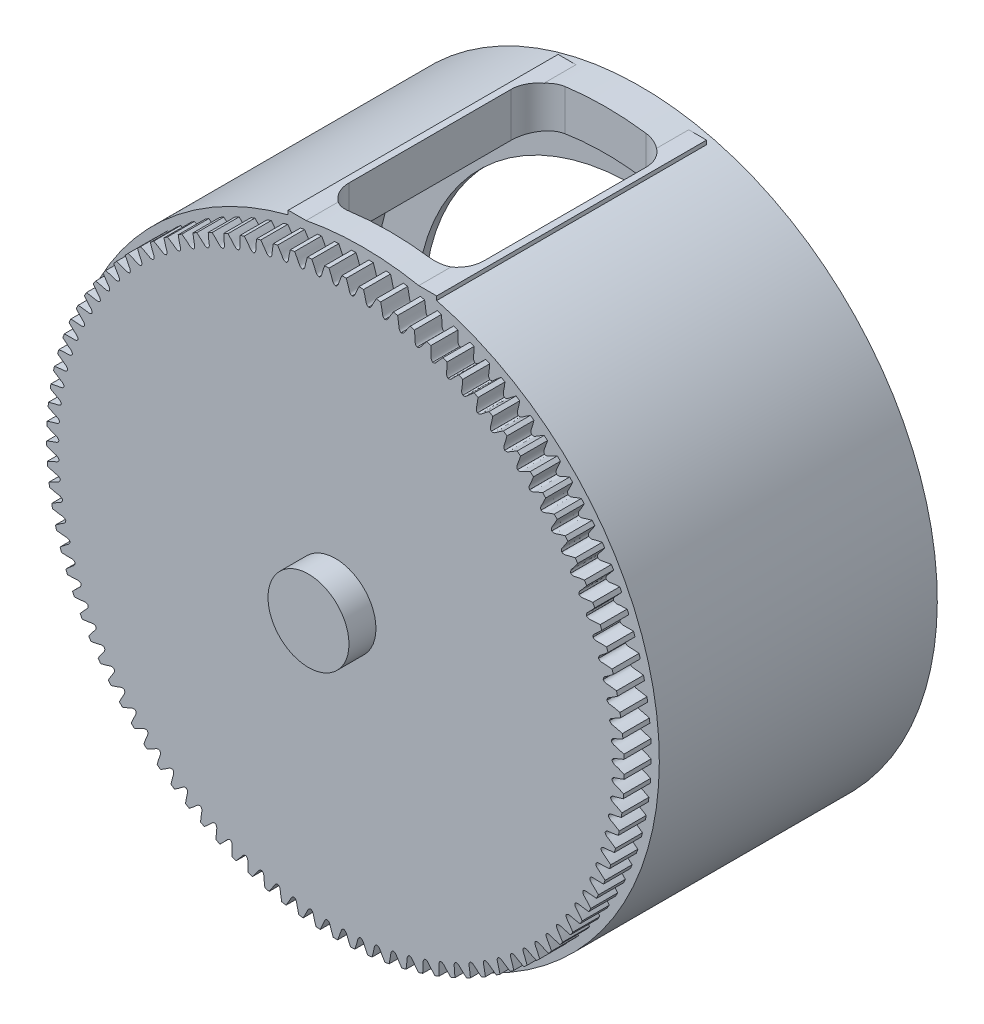
SolidWorks part; units mm, degrees
ref_plane "前视基准面" through (0, 0, 0) normal (0, 0, 1) x (1, 0, 0)
ref_plane "上视基准面" through (0, 0, 0) normal (0, 1, 0) x (1, 0, 0)
ref_plane "右视基准面" through (0, 0, 0) normal (1, 0, 0) x (0, 0, -1)
sketch "草图1" plane through (0, 0, 0) normal (0, 0, 1) x (1, 0, 0)
  circle A0 centre (0, 0) radius 95
  circle A1 centre (0, 0) radius 110
  dimension "D1" = 190
  dimension "D2" = 220
extrude "凸台-拉伸1" add sketch "草图1" along normal mid plane 100
sketch "草图3" plane through (0, 0, 50) normal (0, 0, 1) x (1, 0, 0)
  line L1 (0, -58) -> (0, -52) construction
  circle A2 centre (0, 0) radius 98
  circle A3 centre (0, 0) radius 98
  circle A5 centre (0, 0) radius 107
  circle A6 centre (0, 0) radius 107
  dimension "D1" = 3
  dimension "D2" = 3
extrude "切除-拉伸2" cut sketch "草图3" against normal blind 47
sketch "草图4" plane through (0, 0, 0) normal (0, 1, 0) x (1, 0, 0)
  line L1 (-20, 25) -> (20, 25)
  line L2 (-25, 20) -> (-25, -20)
  line L3 (-20, -25) -> (20, -25)
  line L4 (25, 20) -> (25, -20)
  line L5 (-25, 25) -> (25, -25) construction
  line L6 (-25, -25) -> (25, 25) construction
  line L9 (-10, -2.5) -> (-10, -17.5) construction
  arc A0 (20, 25) -> (25, 20) centre (20, 20) cw
  arc A1 (-25, -20) -> (-20, -25) centre (-20, -20) ccw
  arc A2 (-20, 25) -> (-25, 20) centre (-20, 20) ccw
  arc A3 (20, -25) -> (25, -20) centre (20, -20) ccw
  point P0 (0, 0)
  point P17 (-25, 0)
  point P18 (25, 0)
  dimension "D1" = 50
  dimension "D2" = 50
sketch "草图7" plane through (0, 0, 50) normal (0, 0, 1) x (1, 0, 0)
  circle A0 centre (0, 0) radius 95
  dimension "D1" = 190
sketch "草图25" plane through (0, 0, -50) normal (0, 0, -1) x (-1, 0, 0)
  circle A0 centre (0, 0) radius 106
  circle A1 centre (0, 0) radius 99
  circle A2 centre (0, 0) radius 95 construction
  circle A3 centre (0, 0) radius 110 construction
  dimension "D1" = 4
  dimension "D2" = 4
extrude "切除-拉伸14" cut sketch "草图25" against normal blind 97 and the other way through all
sketch "草图13" plane through (0, 0, 0) normal (0, 1, 0) x (1, 0, 0)
  line L0 (110, 50) -> (-110, 50) construction
  line L1 (-27.5, -50) -> (27.5, -50)
  line L2 (-27.5, -50) -> (-27.5, 50)
  line L3 (-27.5, 50) -> (27.5, 50)
  line L4 (27.5, -50) -> (27.5, 50)
  line L5 (-27.5, -50) -> (27.5, 50) construction
  line L6 (-27.5, 50) -> (27.5, -50) construction
  point P0 (0, 0)
  dimension "D1" = 55
extrude "凸台-拉伸5" add sketch "草图13" along normal blind 108
sketch "草图27" plane through (0, 0, 0) normal (0, -1, 0) x (1, 0, 0)
  line L1 (-15, -40) -> (15, -40)
  line L2 (-25, -30) -> (-25, 30)
  line L3 (-15, 40) -> (15, 40)
  line L4 (25, -30) -> (25, 30)
  line L5 (-25, -40) -> (25, 40) construction
  line L6 (-25, 40) -> (25, -40) construction
  arc A0 (15, -40) -> (25, -30) centre (15, -30) ccw
  arc A1 (-25, 30) -> (-15, 40) centre (-15, 30) cw
  arc A2 (-15, -40) -> (-25, -30) centre (-15, -30) cw
  arc A3 (15, 40) -> (25, 30) centre (15, 30) cw
  point P0 (0, 0)
  dimension "D3" = 10
  dimension "D1" = 80
  dimension "D2" = 50
extrude "切除-拉伸17" cut sketch "草图27" against normal through all
sketch "草图26" plane through (0, 0, -50) normal (0, 0, -1) x (-1, 0, 0)
  circle A0 centre (0, 0) radius 95
extrude "切除-拉伸15" cut sketch "草图26" against normal through all both and the other way through all
sketch "草图14" plane through (0, 0, 0) normal (0, 1, 0) x (1, 0, 0)
  line L1 (59, -47) -> (61, -47)
  line L2 (59, -47) -> (59, 47)
  line L3 (59, 47) -> (61, 47)
  line L4 (61, -47) -> (61, 47)
  line L5 (59, -47) -> (61, 47) construction
  line L6 (59, 47) -> (61, -47) construction
  point P0 (60, 0)
  dimension "D1" = 94
  dimension "D2" = 2
  dimension "D3" = 60
extrude "切除-拉伸12" cut sketch "草图14" along normal blind 85
pattern_circular "阵列(圆周)5" count 8 every 3 about axis through (0, 0, 50) along (0, 0, 1) of "切除-拉伸12" reverse direction yes
sketch "草图15" plane through (0, 0, -50) normal (0, 0, -1) x (-1, 0, 0)
  circle A0 centre (0, 0) radius 110
sketch "草图16" plane through (0, 0, 50) normal (0, 0, 1) x (1, 0, 0)
  circle A0 centre (0, 0) radius 110
extrude "凸台-拉伸6" add sketch "草图16" against normal blind 3
sketch "草图17" plane through (0, 0, -50) normal (0, 0, -1) x (-1, 0, 0)
  circle A0 centre (0, 0) radius 110
  circle A1 centre (0, 0) radius 80
  dimension "D1" = 160
extrude "凸台-拉伸7" add sketch "草图17" along normal blind 3
ref_plane "基准面1" through (90, 0, 0) normal (1, 0, 0) x (0, 0, -1)
sketch "草图19" plane through (90, 0, 0) normal (1, 0, 0) x (0, 0, -1)
  line L0 (53, -110) -> (53, 110) construction
  circle A0 centre (51.5, 0) radius 1.5
  dimension "D1" = 3
  dimension "D2" = 1.5
extrude "凸台-拉伸8" add sketch "草图19" against normal blind 13
mirror "镜向1" about plane through (0, 0, 0) normal (1, 0, 0) of "凸台-拉伸8"
sketch "草图20" plane through (0, 0, 50) normal (0, 0, 1) x (1, 0, 0)
  line L0 (102.4859, 1.5233) -> (102.4856, 1.5433)
  line L1 (102.2114, 7.6497) -> (102.2099, 7.6696)
  line L2 (101.571, 13.7486) -> (101.5683, 13.7685)
  line L3 (100.567, 19.7984) -> (100.5631, 19.818)
  line L4 (99.2029, 25.7773) -> (99.1979, 25.7966)
  line L5 (97.4838, 31.6639) -> (97.4776, 31.6829)
  line L6 (95.4157, 37.4371) -> (95.4084, 37.4558)
  line L7 (93.006, 43.0764) -> (92.9976, 43.0945)
  line L8 (90.2634, 48.5614) -> (90.2539, 48.579)
  line L9 (87.1976, 53.8726) -> (87.1871, 53.8897)
  line L10 (83.8198, 58.991) -> (83.8082, 59.0074)
  line L11 (80.1418, 63.8982) -> (80.1294, 63.9138)
  line L12 (76.177, 68.5766) -> (76.1636, 68.5915)
  line L13 (71.9395, 73.0096) -> (71.9252, 73.0236)
  line L14 (67.4445, 77.1812) -> (67.4294, 77.1943)
  line L15 (62.708, 81.0765) -> (62.6922, 81.0887)
  line L16 (57.747, 84.6816) -> (57.7305, 84.6928)
  line L17 (52.5794, 87.9835) -> (52.5622, 87.9938)
  line L18 (47.2235, 90.9705) -> (47.2057, 90.9797)
  line L19 (41.6985, 93.6318) -> (41.6803, 93.64)
  line L20 (36.0243, 95.958) -> (36.0056, 95.965)
  line L21 (30.2212, 97.9407) -> (30.202, 97.9465)
  line L22 (24.3098, 99.5727) -> (24.2904, 99.5774)
  line L23 (18.3114, 100.8483) -> (18.2918, 100.8519)
  line L24 (12.2475, 101.7629) -> (12.2277, 101.7653)
  line L25 (6.1397, 102.3132) -> (6.1198, 102.3144)
  line L26 (0.01, 102.4973) -> (-0.01, 102.4973)
  line L27 (-6.1198, 102.3144) -> (-6.1397, 102.3132)
  line L28 (-12.2277, 101.7653) -> (-12.2475, 101.7629)
  line L29 (-18.2918, 100.8519) -> (-18.3114, 100.8483)
  line L30 (-24.2904, 99.5774) -> (-24.3098, 99.5727)
  line L31 (-30.202, 97.9465) -> (-30.2212, 97.9407)
  line L32 (-36.0056, 95.965) -> (-36.0243, 95.958)
  line L33 (-41.6803, 93.64) -> (-41.6985, 93.6318)
  line L34 (-47.2057, 90.9797) -> (-47.2235, 90.9705)
  line L35 (-52.5622, 87.9938) -> (-52.5794, 87.9835)
  line L36 (-57.7305, 84.6928) -> (-57.747, 84.6816)
  line L37 (-62.6922, 81.0887) -> (-62.708, 81.0765)
  line L38 (-67.4294, 77.1943) -> (-67.4445, 77.1812)
  line L39 (-71.9252, 73.0236) -> (-71.9395, 73.0096)
  line L40 (-76.1636, 68.5915) -> (-76.177, 68.5766)
  line L41 (-80.1294, 63.9138) -> (-80.1418, 63.8982)
  line L42 (-83.8082, 59.0074) -> (-83.8198, 58.991)
  line L43 (-87.1871, 53.8897) -> (-87.1976, 53.8726)
  line L44 (-90.2539, 48.579) -> (-90.2634, 48.5614)
  line L45 (-92.9976, 43.0945) -> (-93.006, 43.0764)
  line L46 (-95.4084, 37.4558) -> (-95.4157, 37.4371)
  line L47 (-97.4776, 31.6829) -> (-97.4838, 31.6639)
  line L48 (-99.1979, 25.7966) -> (-99.2029, 25.7773)
  line L49 (-100.5631, 19.818) -> (-100.567, 19.7984)
  line L50 (-101.5683, 13.7685) -> (-101.571, 13.7486)
  line L51 (-102.2099, 7.6696) -> (-102.2114, 7.6497)
  line L52 (-102.4856, 1.5433) -> (-102.4859, 1.5233)
  line L53 (-102.3945, -4.5885) -> (-102.3936, -4.6085)
  line L54 (-101.9368, -10.7039) -> (-101.9347, -10.7238)
  line L55 (-101.1142, -16.781) -> (-101.111, -16.8008)
  line L56 (-99.9297, -22.798) -> (-99.9252, -22.8175)
  line L57 (-98.3874, -28.7334) -> (-98.3818, -28.7526)
  line L58 (-96.4929, -34.566) -> (-96.4862, -34.5848)
  line L59 (-94.253, -40.2748) -> (-94.2452, -40.2932)
  line L60 (-91.6757, -45.8394) -> (-91.6668, -45.8573)
  line L61 (-88.7702, -51.24) -> (-88.7602, -51.2573)
  line L62 (-85.547, -56.4571) -> (-85.536, -56.4738)
  line L63 (-82.0175, -61.4721) -> (-82.0055, -61.4881)
  line L64 (-78.1944, -66.2671) -> (-78.1815, -66.2823)
  line L65 (-74.0914, -70.8248) -> (-74.0776, -70.8393)
  line L66 (-69.7232, -75.129) -> (-69.7085, -75.1426)
  line L67 (-65.1054, -79.1643) -> (-65.0899, -79.177)
  line L68 (-60.2545, -82.9162) -> (-60.2383, -82.9279)
  line L69 (-55.1879, -86.3712) -> (-55.171, -86.382)
  line L70 (-49.9238, -89.5171) -> (-49.9063, -89.5268)
  line L71 (-44.4809, -92.3425) -> (-44.4629, -92.3512)
  line L72 (-38.8788, -94.8374) -> (-38.8603, -94.845)
  line L73 (-33.1376, -96.9927) -> (-33.1186, -96.9992)
  line L74 (-27.2777, -98.8009) -> (-27.2584, -98.8062)
  line L75 (-21.3202, -100.2554) -> (-21.3006, -100.2595)
  line L76 (-15.2863, -101.351) -> (-15.2665, -101.3539)
  line L77 (-9.1977, -102.0837) -> (-9.1778, -102.0855)
  line L78 (-3.0762, -102.4511) -> (-3.0563, -102.4517)
  line L79 (3.0563, -102.4517) -> (3.0762, -102.4511)
  line L80 (9.1778, -102.0855) -> (9.1977, -102.0837)
  line L81 (15.2665, -101.3539) -> (15.2863, -101.351)
  line L82 (21.3006, -100.2595) -> (21.3202, -100.2554)
  line L83 (27.2584, -98.8062) -> (27.2777, -98.8009)
  line L84 (33.1186, -96.9992) -> (33.1376, -96.9927)
  line L85 (38.8603, -94.845) -> (38.8788, -94.8374)
  line L86 (44.4629, -92.3512) -> (44.4809, -92.3425)
  line L87 (49.9063, -89.5268) -> (49.9238, -89.5171)
  line L88 (55.171, -86.382) -> (55.1879, -86.3712)
  line L89 (60.2383, -82.9279) -> (60.2545, -82.9162)
  line L90 (65.0899, -79.177) -> (65.1054, -79.1643)
  line L91 (69.7085, -75.1426) -> (69.7232, -75.129)
  line L92 (74.0776, -70.8393) -> (74.0914, -70.8248)
  line L93 (78.1815, -66.2823) -> (78.1944, -66.2671)
  line L94 (82.0055, -61.4881) -> (82.0175, -61.4721)
  line L95 (85.536, -56.4738) -> (85.547, -56.4571)
  line L96 (88.7602, -51.2573) -> (88.7702, -51.24)
  line L97 (91.6668, -45.8573) -> (91.6757, -45.8394)
  line L98 (94.2452, -40.2932) -> (94.253, -40.2748)
  line L99 (96.4862, -34.5848) -> (96.4929, -34.566)
  line L100 (98.3818, -28.7526) -> (98.3874, -28.7334)
  line L101 (99.9252, -22.8175) -> (99.9297, -22.798)
  line L102 (101.111, -16.8008) -> (101.1142, -16.781)
  line L103 (101.9347, -10.7238) -> (101.9368, -10.7039)
  line L104 (102.3936, -4.6085) -> (102.3945, -4.5885)
  arc A0 (106.9729, -2.4093) -> (106.9971, -0.792) centre (0, 0) ccw
  arc A1 (106.9255, 3.9925) -> (106.8529, 5.6083) centre (0, 0) ccw
  arc A2 (106.4953, 10.3799) -> (106.3263, 11.9885) centre (0, 0) ccw
  arc A3 (105.684, 16.7302) -> (105.419, 18.3258) centre (0, 0) ccw
  arc A4 (104.4943, 23.0206) -> (104.1343, 24.5975) centre (0, 0) ccw
  arc A5 (102.9305, 29.2286) -> (102.4769, 30.7812) centre (0, 0) ccw
  arc A6 (100.9983, 35.3319) -> (100.4527, 36.8546) centre (0, 0) ccw
  arc A7 (98.7045, 41.3088) -> (98.0688, 42.7961) centre (0, 0) ccw
  arc A8 (96.0574, 47.1378) -> (95.3339, 48.5845) centre (0, 0) ccw
  arc A9 (93.0664, 52.7981) -> (92.2577, 54.1989) centre (0, 0) ccw
  arc A10 (89.7423, 58.2693) -> (88.8513, 59.6192) centre (0, 0) ccw
  arc A11 (86.0969, 63.532) -> (85.1267, 64.8262) centre (0, 0) ccw
  arc A12 (82.1434, 68.5673) -> (81.0975, 69.8011) centre (0, 0) ccw
  arc A13 (77.8957, 73.357) -> (76.778, 74.5261) centre (0, 0) ccw
  arc A14 (73.3692, 77.8842) -> (72.1836, 78.9844) centre (0, 0) ccw
  arc A15 (68.5801, 82.1326) -> (67.3308, 83.1599) centre (0, 0) ccw
  arc A16 (63.5455, 86.087) -> (62.2369, 87.0377) centre (0, 0) ccw
  arc A17 (58.2834, 89.7332) -> (56.9203, 90.6039) centre (0, 0) ccw
  arc A18 (52.8127, 93.0582) -> (51.4, 93.8459) centre (0, 0) ccw
  arc A19 (47.1529, 96.05) -> (45.6956, 96.7518) centre (0, 0) ccw
  arc A20 (41.3243, 98.698) -> (39.8276, 99.3114) centre (0, 0) ccw
  arc A21 (35.3478, 100.9927) -> (33.8171, 101.5155) centre (0, 0) ccw
  arc A22 (29.2447, 102.9259) -> (27.6855, 103.3562) centre (0, 0) ccw
  arc A23 (23.037, 104.4907) -> (21.4549, 104.8269) centre (0, 0) ccw
  arc A24 (16.7468, 105.6813) -> (15.1474, 105.9224) centre (0, 0) ccw
  arc A25 (10.3966, 106.4937) -> (8.7857, 106.6387) centre (0, 0) ccw
  arc A26 (4.0092, 106.9249) -> (2.3925, 106.9732) centre (0, 0) ccw
  arc A27 (-2.3925, 106.9732) -> (-4.0092, 106.9249) centre (0, 0) ccw
  arc A28 (-8.7857, 106.6387) -> (-10.3966, 106.4937) centre (0, 0) ccw
  arc A29 (-15.1474, 105.9224) -> (-16.7468, 105.6813) centre (0, 0) ccw
  arc A30 (-21.4549, 104.8269) -> (-23.037, 104.4907) centre (0, 0) ccw
  arc A31 (-27.6855, 103.3562) -> (-29.2447, 102.9259) centre (0, 0) ccw
  arc A32 (-33.8171, 101.5155) -> (-35.3478, 100.9927) centre (0, 0) ccw
  arc A33 (-39.8276, 99.3114) -> (-41.3243, 98.698) centre (0, 0) ccw
  arc A34 (-45.6956, 96.7518) -> (-47.1529, 96.05) centre (0, 0) ccw
  arc A35 (-51.4, 93.8459) -> (-52.8127, 93.0582) centre (0, 0) ccw
  arc A36 (-56.9203, 90.6039) -> (-58.2834, 89.7332) centre (0, 0) ccw
  arc A37 (-62.2369, 87.0377) -> (-63.5455, 86.087) centre (0, 0) ccw
  arc A38 (-67.3308, 83.1599) -> (-68.5801, 82.1326) centre (0, 0) ccw
  arc A39 (-72.1836, 78.9844) -> (-73.3692, 77.8842) centre (0, 0) ccw
  arc A40 (-76.778, 74.5261) -> (-77.8957, 73.357) centre (0, 0) ccw
  arc A41 (-81.0975, 69.8011) -> (-82.1434, 68.5673) centre (0, 0) ccw
  arc A42 (-85.1267, 64.8262) -> (-86.0969, 63.532) centre (0, 0) ccw
  arc A43 (-88.8513, 59.6192) -> (-89.7423, 58.2693) centre (0, 0) ccw
  arc A44 (-92.2577, 54.1989) -> (-93.0664, 52.7981) centre (0, 0) ccw
  arc A45 (-95.3339, 48.5845) -> (-96.0574, 47.1378) centre (0, 0) ccw
  arc A46 (-98.0688, 42.7961) -> (-98.7045, 41.3088) centre (0, 0) ccw
  arc A47 (-100.4527, 36.8546) -> (-100.9983, 35.3319) centre (0, 0) ccw
  arc A48 (-102.4769, 30.7812) -> (-102.9305, 29.2286) centre (0, 0) ccw
  arc A49 (-104.1343, 24.5975) -> (-104.4943, 23.0206) centre (0, 0) ccw
  arc A50 (-105.419, 18.3258) -> (-105.684, 16.7302) centre (0, 0) ccw
  arc A51 (-106.3263, 11.9885) -> (-106.4953, 10.3799) centre (0, 0) ccw
  arc A52 (-106.8529, 5.6083) -> (-106.9255, 3.9925) centre (0, 0) ccw
  arc A53 (-106.9971, -0.792) -> (-106.9729, -2.4093) centre (0, 0) ccw
  arc A54 (-106.7582, -7.1894) -> (-106.6373, -8.8024) centre (0, 0) ccw
  arc A55 (-106.1372, -13.5611) -> (-105.92, -15.164) centre (0, 0) ccw
  arc A56 (-105.1362, -19.8843) -> (-104.8236, -21.4713) centre (0, 0) ccw
  arc A57 (-103.7588, -26.1363) -> (-103.3519, -27.7017) centre (0, 0) ccw
  arc A58 (-102.0101, -32.2947) -> (-101.5102, -33.833) centre (0, 0) ccw
  arc A59 (-99.8961, -38.3375) -> (-99.3052, -39.8432) centre (0, 0) ccw
  arc A60 (-97.4246, -44.2431) -> (-96.7446, -45.7108) centre (0, 0) ccw
  arc A61 (-94.6043, -49.9903) -> (-93.8378, -51.4147) centre (0, 0) ccw
  arc A62 (-91.4453, -55.5586) -> (-90.595, -56.9345) centre (0, 0) ccw
  arc A63 (-87.959, -60.9279) -> (-87.028, -62.2506) centre (0, 0) ccw
  arc A64 (-84.1578, -66.0792) -> (-83.1493, -67.3438) centre (0, 0) ccw
  arc A65 (-80.0554, -70.9939) -> (-78.9731, -72.1959) centre (0, 0) ccw
  arc A66 (-75.6664, -75.6545) -> (-74.5141, -76.7896) centre (0, 0) ccw
  arc A67 (-71.0065, -80.0442) -> (-69.7884, -81.1084) centre (0, 0) ccw
  arc A68 (-66.0924, -84.1475) -> (-64.8129, -85.1369) centre (0, 0) ccw
  arc A69 (-60.9417, -87.9494) -> (-59.6053, -88.8606) centre (0, 0) ccw
  arc A70 (-55.5729, -91.4366) -> (-54.1844, -92.2662) centre (0, 0) ccw
  arc A71 (-50.0052, -94.5964) -> (-48.5695, -95.3415) centre (0, 0) ccw
  arc A72 (-44.2584, -97.4176) -> (-42.7808, -98.0755) centre (0, 0) ccw
  arc A73 (-38.3532, -99.8901) -> (-36.8389, -100.4584) centre (0, 0) ccw
  arc A74 (-32.3107, -102.005) -> (-30.7651, -102.4817) centre (0, 0) ccw
  arc A75 (-26.1526, -103.7547) -> (-24.5812, -104.1382) centre (0, 0) ccw
  arc A76 (-19.9008, -105.1331) -> (-18.3093, -105.4219) centre (0, 0) ccw
  arc A77 (-13.5778, -106.135) -> (-11.9719, -106.3281) centre (0, 0) ccw
  arc A78 (-7.2061, -106.7571) -> (-5.5916, -106.8538) centre (0, 0) ccw
  arc A79 (-0.8087, -106.9969) -> (0.8087, -106.9969) centre (0, 0) ccw
  arc A80 (5.5916, -106.8538) -> (7.2061, -106.7571) centre (0, 0) ccw
  arc A81 (11.9719, -106.3281) -> (13.5778, -106.135) centre (0, 0) ccw
  arc A82 (18.3093, -105.4219) -> (19.9008, -105.1331) centre (0, 0) ccw
  arc A83 (24.5812, -104.1382) -> (26.1526, -103.7547) centre (0, 0) ccw
  arc A84 (30.7651, -102.4817) -> (32.3107, -102.005) centre (0, 0) ccw
  arc A85 (36.8389, -100.4584) -> (38.3532, -99.8901) centre (0, 0) ccw
  arc A86 (42.7808, -98.0755) -> (44.2584, -97.4176) centre (0, 0) ccw
  arc A87 (48.5695, -95.3415) -> (50.0052, -94.5964) centre (0, 0) ccw
  arc A88 (54.1844, -92.2662) -> (55.5729, -91.4366) centre (0, 0) ccw
  arc A89 (59.6053, -88.8606) -> (60.9417, -87.9494) centre (0, 0) ccw
  arc A90 (64.8129, -85.1369) -> (66.0924, -84.1475) centre (0, 0) ccw
  arc A91 (69.7884, -81.1084) -> (71.0065, -80.0442) centre (0, 0) ccw
  arc A92 (74.5141, -76.7896) -> (75.6664, -75.6545) centre (0, 0) ccw
  arc A93 (78.9731, -72.1959) -> (80.0554, -70.9939) centre (0, 0) ccw
  arc A94 (83.1493, -67.3438) -> (84.1578, -66.0792) centre (0, 0) ccw
  arc A95 (87.028, -62.2506) -> (87.959, -60.9279) centre (0, 0) ccw
  arc A96 (90.595, -56.9345) -> (91.4453, -55.5586) centre (0, 0) ccw
  arc A97 (93.8378, -51.4147) -> (94.6043, -49.9903) centre (0, 0) ccw
  arc A98 (96.7446, -45.7108) -> (97.4246, -44.2431) centre (0, 0) ccw
  arc A99 (99.3052, -39.8432) -> (99.8961, -38.3375) centre (0, 0) ccw
  arc A100 (101.5102, -33.833) -> (102.0101, -32.2947) centre (0, 0) ccw
  arc A101 (103.3519, -27.7017) -> (103.7588, -26.1363) centre (0, 0) ccw
  arc A102 (104.8236, -21.4713) -> (105.1362, -19.8843) centre (0, 0) ccw
  arc A103 (105.92, -15.164) -> (106.1372, -13.5611) centre (0, 0) ccw
  arc A104 (106.6373, -8.8024) -> (106.7582, -7.1894) centre (0, 0) ccw
  spline S0 degree 3 poles (106.9971, -0.792) (106.9945, -0.7909) (106.7444, -0.6838) (106.2568, -0.4808) (105.542, -0.199) (104.8574, 0.0522) (103.7383, 0.4548) (102.7847, 0.6503) (102.4859, 1.5233) knots 0 0 0 0 0.000356 0.034813 0.067588 0.098678 0.128086 0.220071 0.220071 0.220071 0.220071
  spline S1 degree 3 poles (102.4856, 1.5433) (102.7582, 2.4249) (103.7055, 2.6488) (104.8121, 3.0846) (105.4888, 3.3563) (106.1948, 3.6593) (106.6762, 3.8768) (106.923, 3.9913) (106.9255, 3.9925) knots 0.779929 0.779929 0.779929 0.779929 0.871914 0.901322 0.932412 0.965187 0.999644 1 1 1 1
  spline S2 degree 3 poles (106.8529, 5.6083) (106.8503, 5.6093) (106.5943, 5.7012) (106.0954, 5.8746) (105.365, 6.1132) (104.6666, 6.3231) (103.5254, 6.658) (102.5619, 6.7961) (102.2114, 7.6497) knots 0 0 0 0 0.000356 0.034813 0.067588 0.098678 0.128086 0.220071 0.220071 0.220071 0.220071
  spline S3 degree 3 poles (102.2099, 7.6696) (102.4292, 8.5659) (103.3615, 8.846) (104.44, 9.3473) (105.0993, 9.659) (105.7859, 10.0037) (106.2534, 10.2496) (106.4929, 10.3786) (106.4953, 10.3799) knots 0.779929 0.779929 0.779929 0.779929 0.871914 0.901322 0.932412 0.965187 0.999644 1 1 1 1
  spline S4 degree 3 poles (106.3263, 11.9885) (106.3236, 11.9893) (106.0625, 12.0657) (105.5541, 12.2091) (104.8109, 12.4035) (104.1011, 12.5712) (102.942, 12.8373) (101.9719, 12.9175) (101.571, 13.7486) knots 0 0 0 0 0.000356 0.034813 0.067588 0.098678 0.128086 0.220071 0.220071 0.220071 0.220071
  spline S5 degree 3 poles (101.5683, 13.7685) (101.7336, 14.6762) (102.6474, 15.0116) (103.6941, 15.5765) (104.3336, 15.9271) (104.9983, 16.3122) (105.4503, 16.5856) (105.6816, 16.7287) (105.684, 16.7302) knots 0.779929 0.779929 0.779929 0.779929 0.871914 0.901322 0.932412 0.965187 0.999644 1 1 1 1
  spline S6 degree 3 poles (105.419, 18.3258) (105.4163, 18.3264) (105.1511, 18.3871) (104.635, 18.4998) (103.8815, 18.6494) (103.163, 18.7744) (101.99, 18.9707) (101.0168, 18.9928) (100.567, 19.7984) knots 0 0 0 0 0.000356 0.034813 0.067588 0.098678 0.128086 0.220071 0.220071 0.220071 0.220071
  spline S7 degree 3 poles (100.5631, 19.818) (100.6738, 20.7341) (101.566, 21.1235) (102.5769, 21.75) (103.1943, 22.1381) (103.8349, 22.5623) (104.2696, 22.8623) (104.492, 23.019) (104.4943, 23.0206) knots 0.779929 0.779929 0.779929 0.779929 0.871914 0.901322 0.932412 0.965187 0.999644 1 1 1 1
  spline S8 degree 3 poles (104.1343, 24.5975) (104.1316, 24.598) (103.8633, 24.6427) (103.3414, 24.7243) (102.5802, 24.8286) (101.8556, 24.9104) (100.6729, 25.0362) (99.7002, 25) (99.2029, 25.7773) knots 0 0 0 0 0.000356 0.034813 0.067588 0.098678 0.128086 0.220071 0.220071 0.220071 0.220071
  spline S9 degree 3 poles (99.1979, 25.7966) (99.2537, 26.7177) (100.1209, 27.1598) (101.0926, 27.8456) (101.6857, 28.2699) (102.2997, 28.7317) (102.7157, 29.0571) (102.9283, 29.2269) (102.9305, 29.2286) knots 0.779929 0.779929 0.779929 0.779929 0.871914 0.901322 0.932412 0.965187 0.999644 1 1 1 1
  spline S10 degree 3 poles (102.4769, 30.7812) (102.4742, 30.7814) (102.2036, 30.81) (101.6778, 30.8603) (100.9118, 30.9189) (100.1835, 30.9572) (98.9955, 31.012) (98.0266, 30.9177) (97.4838, 31.6639) knots 0 0 0 0 0.000356 0.034813 0.067588 0.098678 0.128086 0.220071 0.220071 0.220071 0.220071
  spline S11 degree 3 poles (97.4776, 31.6829) (97.4782, 32.6056) (98.3174, 33.0988) (99.2464, 33.8415) (99.813, 34.3006) (100.3983, 34.7982) (100.7942, 35.1479) (100.9962, 35.3301) (100.9983, 35.3319) knots 0.779929 0.779929 0.779929 0.779929 0.871914 0.901322 0.932412 0.965187 0.999644 1 1 1 1
  spline S12 degree 3 poles (100.4527, 36.8546) (100.4499, 36.8547) (100.1781, 36.8671) (99.6503, 36.8858) (98.8821, 36.8985) (98.1528, 36.8932) (96.9636, 36.8769) (96.0021, 36.7248) (95.4157, 37.4371) knots 0 0 0 0 0.000356 0.034813 0.067588 0.098678 0.128086 0.220071 0.220071 0.220071 0.220071
  spline S13 degree 3 poles (95.4084, 37.4558) (95.3538, 38.3769) (96.162, 38.9194) (97.0449, 39.7163) (97.583, 40.2084) (98.1375, 40.7402) (98.5117, 41.1129) (98.7026, 41.3068) (98.7045, 41.3088) knots 0.779929 0.779929 0.779929 0.779929 0.871914 0.901322 0.932412 0.965187 0.999644 1 1 1 1
  spline S14 degree 3 poles (98.0688, 42.7961) (98.066, 42.7961) (97.794, 42.7922) (97.266, 42.7793) (96.4984, 42.746) (95.7708, 42.6971) (94.5847, 42.6097) (93.634, 42.4004) (93.006, 43.0764) knots 0 0 0 0 0.000356 0.034813 0.067588 0.098678 0.128086 0.220071 0.220071 0.220071 0.220071
  spline S15 degree 3 poles (92.9976, 43.0945) (92.888, 44.0107) (93.6623, 44.6006) (94.496, 45.4489) (95.0037, 45.9723) (95.5254, 46.5363) (95.8767, 46.9308) (96.0556, 47.1357) (96.0574, 47.1378) knots 0.779929 0.779929 0.779929 0.779929 0.871914 0.901322 0.932412 0.965187 0.999644 1 1 1 1
  spline S16 degree 3 poles (95.3339, 48.5845) (95.3311, 48.5842) (95.0598, 48.5641) (94.5335, 48.5196) (93.7693, 48.4405) (93.0459, 48.3482) (91.8671, 48.19) (90.9307, 47.9242) (90.2634, 48.5614) knots 0 0 0 0 0.000356 0.034813 0.067588 0.098678 0.128086 0.220071 0.220071 0.220071 0.220071
  spline S17 degree 3 poles (90.2539, 48.579) (90.0897, 49.487) (90.8274, 50.1222) (91.6088, 51.0188) (92.0843, 51.5716) (92.5714, 52.1658) (92.8984, 52.5806) (93.0647, 52.7959) (93.0664, 52.7981) knots 0.779929 0.779929 0.779929 0.779929 0.871914 0.901322 0.932412 0.965187 0.999644 1 1 1 1
  spline S18 degree 3 poles (92.2577, 54.1989) (92.255, 54.1985) (91.9853, 54.1621) (91.4626, 54.0863) (90.7045, 53.9616) (89.9879, 53.8262) (88.8208, 53.5978) (87.9019, 53.2765) (87.1976, 53.8726) knots 0 0 0 0 0.000356 0.034813 0.067588 0.098678 0.128086 0.220071 0.220071 0.220071 0.220071
  spline S19 degree 3 poles (87.1871, 53.8897) (86.9689, 54.7862) (87.6673, 55.4643) (88.3937, 56.406) (88.8353, 56.9864) (89.286, 57.6086) (89.5876, 58.0422) (89.7408, 58.267) (89.7423, 58.2693) knots 0.779929 0.779929 0.779929 0.779929 0.871914 0.901322 0.932412 0.965187 0.999644 1 1 1 1
  spline S20 degree 3 poles (88.8513, 59.6192) (88.8485, 59.6187) (88.5816, 59.5663) (88.0643, 59.4593) (87.3151, 59.2895) (86.6079, 59.1115) (85.4564, 58.8137) (84.5584, 58.438) (83.8198, 58.991) knots 0 0 0 0 0.000356 0.034813 0.067588 0.098678 0.128086 0.220071 0.220071 0.220071 0.220071
  spline S21 degree 3 poles (83.8082, 59.0074) (83.5368, 59.8893) (84.1934, 60.6079) (84.8622, 61.5914) (85.2683, 62.1971) (85.6809, 62.8452) (85.9561, 63.296) (86.0955, 63.5296) (86.0969, 63.532) knots 0.779929 0.779929 0.779929 0.779929 0.871914 0.901322 0.932412 0.965187 0.999644 1 1 1 1
  spline S22 degree 3 poles (85.1267, 64.8262) (85.1241, 64.8255) (84.8607, 64.7572) (84.3508, 64.6195) (83.613, 64.4052) (82.9177, 64.1852) (81.7862, 63.8191) (80.9122, 63.3903) (80.1418, 63.8982) knots 0 0 0 0 0.000356 0.034813 0.067588 0.098678 0.128086 0.220071 0.220071 0.220071 0.220071
  spline S23 degree 3 poles (80.1294, 63.9138) (79.8057, 64.7779) (80.4181, 65.5345) (81.0268, 66.5563) (81.396, 67.1852) (81.7692, 67.8568) (82.0169, 68.3233) (82.1421, 68.5648) (82.1434, 68.5673) knots 0.779929 0.779929 0.779929 0.779929 0.871914 0.901322 0.932412 0.965187 0.999644 1 1 1 1
  spline S24 degree 3 poles (81.0975, 69.8011) (81.0949, 69.8003) (80.8361, 69.7163) (80.3353, 69.5484) (79.6117, 69.2903) (78.9308, 69.0291) (77.8231, 68.596) (76.9764, 68.1158) (76.177, 68.5766) knots 0 0 0 0 0.000356 0.034813 0.067588 0.098678 0.128086 0.220071 0.220071 0.220071 0.220071
  spline S25 degree 3 poles (76.1636, 68.5915) (75.7888, 69.4347) (76.3549, 70.2266) (76.9015, 71.2829) (77.2324, 71.9327) (77.5647, 72.6254) (77.7841, 73.1059) (77.8946, 73.3545) (77.8957, 73.357) knots 0.779929 0.779929 0.779929 0.779929 0.871914 0.901322 0.932412 0.965187 0.999644 1 1 1 1
  spline S26 degree 3 poles (76.778, 74.5261) (76.7754, 74.5251) (76.5221, 74.4259) (76.0322, 74.2283) (75.3253, 73.9274) (74.6613, 73.626) (73.5815, 73.1273) (72.765, 72.5974) (71.9395, 73.0096) knots 0 0 0 0 0.000356 0.034813 0.067588 0.098678 0.128086 0.220071 0.220071 0.220071 0.220071
  spline S27 degree 3 poles (71.9252, 73.0236) (71.5007, 73.8429) (72.0184, 74.6672) (72.5008, 75.7543) (72.7923, 76.4228) (73.0826, 77.1341) (73.2728, 77.6269) (73.3683, 77.8816) (73.3692, 77.8842) knots 0.779929 0.779929 0.779929 0.779929 0.871914 0.901322 0.932412 0.965187 0.999644 1 1 1 1
  spline S28 degree 3 poles (72.1836, 78.9844) (72.181, 78.9832) (71.9341, 78.869) (71.457, 78.6425) (70.7693, 78.2998) (70.1245, 77.9592) (69.0765, 77.3969) (68.2931, 76.8191) (67.4445, 77.1812) knots 0 0 0 0 0.000356 0.034813 0.067588 0.098678 0.128086 0.220071 0.220071 0.220071 0.220071
  spline S29 degree 3 poles (67.4294, 77.1943) (66.9566, 77.9868) (67.4241, 78.8406) (67.8406, 79.9546) (68.0916, 80.6393) (68.3388, 81.3667) (68.4993, 81.87) (68.5793, 82.13) (68.5801, 82.1326) knots 0.779929 0.779929 0.779929 0.779929 0.871914 0.901322 0.932412 0.965187 0.999644 1 1 1 1
  spline S30 degree 3 poles (67.3308, 83.1599) (67.3283, 83.1586) (67.0887, 83.0298) (66.6259, 82.7751) (65.96, 82.392) (65.3367, 82.0134) (64.3242, 81.3895) (63.5768, 80.7658) (62.708, 81.0765) knots 0 0 0 0 0.000356 0.034813 0.067588 0.098678 0.128086 0.220071 0.220071 0.220071 0.220071
  spline S31 degree 3 poles (62.6922, 81.0887) (62.1728, 81.8514) (62.5884, 82.7317) (62.9376, 83.8686) (63.1472, 84.5671) (63.3504, 85.308) (63.4805, 85.82) (63.5448, 86.0843) (63.5455, 86.087) knots 0.779929 0.779929 0.779929 0.779929 0.871914 0.901322 0.932412 0.965187 0.999644 1 1 1 1
  spline S32 degree 3 poles (62.2369, 87.0377) (62.2346, 87.0362) (62.0031, 86.8934) (61.5564, 86.6115) (60.9146, 86.1892) (60.315, 85.774) (59.3416, 85.0906) (58.6329, 84.4234) (57.747, 84.6816) knots 0 0 0 0 0.000356 0.034813 0.067588 0.098678 0.128086 0.220071 0.220071 0.220071 0.220071
  spline S33 degree 3 poles (57.7305, 84.6928) (57.1665, 85.4231) (57.5287, 86.3267) (57.8093, 87.4824) (57.9767, 88.1922) (58.1353, 88.944) (58.2345, 89.4627) (58.2829, 89.7305) (58.2834, 89.7332) knots 0.779929 0.779929 0.779929 0.779929 0.871914 0.901322 0.932412 0.965187 0.999644 1 1 1 1
  spline S34 degree 3 poles (56.9203, 90.6039) (56.9181, 90.6024) (56.6955, 90.4459) (56.2665, 90.1378) (55.6511, 89.6779) (55.0774, 89.2276) (54.1466, 88.4872) (53.4791, 87.7788) (52.5794, 87.9835) knots 0 0 0 0 0.000356 0.034813 0.067588 0.098678 0.128086 0.220071 0.220071 0.220071 0.220071
  spline S35 degree 3 poles (52.5622, 87.9938) (51.9555, 88.689) (52.2631, 89.6126) (52.474, 90.7831) (52.5986, 91.5016) (52.712, 92.2615) (52.78, 92.7853) (52.8123, 93.0554) (52.8127, 93.0582) knots 0.779929 0.779929 0.779929 0.779929 0.871914 0.901322 0.932412 0.965187 0.999644 1 1 1 1
  spline S36 degree 3 poles (51.4, 93.8459) (51.3978, 93.8441) (51.185, 93.6746) (50.7752, 93.3414) (50.1883, 92.8455) (49.6426, 92.3618) (48.7578, 91.567) (48.1338, 90.8199) (47.2235, 90.9705) knots 0 0 0 0 0.000356 0.034813 0.067588 0.098678 0.128086 0.220071 0.220071 0.220071 0.220071
  spline S37 degree 3 poles (47.2057, 90.9797) (46.5586, 91.6375) (46.8103, 92.5778) (46.9508, 93.7588) (47.0323, 94.4835) (47.1, 95.2487) (47.1366, 95.7757) (47.1527, 96.0472) (47.1529, 96.05) knots 0.779929 0.779929 0.779929 0.779929 0.871914 0.901322 0.932412 0.965187 0.999644 1 1 1 1
  spline S38 degree 3 poles (45.6956, 96.7518) (45.6935, 96.75) (45.4913, 96.568) (45.1021, 96.2109) (44.546, 95.6808) (44.0302, 95.1653) (43.1945, 94.3191) (42.6163, 93.536) (41.6985, 93.6318) knots 0 0 0 0 0.000356 0.034813 0.067588 0.098678 0.128086 0.220071 0.220071 0.220071 0.220071
  spline S39 degree 3 poles (41.6803, 93.64) (40.9949, 94.2578) (41.19, 95.2115) (41.2596, 96.3988) (41.2976, 97.1271) (41.3195, 97.895) (41.3244, 98.4232) (41.3243, 98.6953) (41.3243, 98.698) knots 0.779929 0.779929 0.779929 0.779929 0.871914 0.901322 0.932412 0.965187 0.999644 1 1 1 1
  spline S40 degree 3 poles (39.8276, 99.3114) (39.8257, 99.3094) (39.6347, 99.1158) (39.2675, 98.736) (38.7441, 98.1736) (38.2601, 97.6281) (37.4765, 96.7334) (36.9461, 95.9172) (36.0243, 95.958) knots 0 0 0 0 0.000356 0.034813 0.067588 0.098678 0.128086 0.220071 0.220071 0.220071 0.220071
  spline S41 degree 3 poles (36.0056, 95.965) (35.2845, 96.5408) (35.4222, 97.5044) (35.4207, 98.6938) (35.4151, 99.423) (35.391, 100.1909) (35.3644, 100.7184) (35.3479, 100.99) (35.3478, 100.9927) knots 0.779929 0.779929 0.779929 0.779929 0.871914 0.901322 0.932412 0.965187 0.999644 1 1 1 1
  spline S42 degree 3 poles (33.8171, 101.5155) (33.8153, 101.5134) (33.6362, 101.3087) (33.2924, 100.9076) (32.8036, 100.3149) (32.353, 99.7415) (31.6243, 98.8016) (31.1438, 97.955) (30.2212, 97.9407) knots 0 0 0 0 0.000356 0.034813 0.067588 0.098678 0.128086 0.220071 0.220071 0.220071 0.220071
  spline S43 degree 3 poles (30.202, 97.9465) (29.4478, 98.4782) (29.5276, 99.4483) (29.4551, 100.6354) (29.4058, 101.363) (29.3358, 102.1281) (29.2777, 102.6531) (29.2451, 102.9232) (29.2447, 102.9259) knots 0.779929 0.779929 0.779929 0.779929 0.871914 0.901322 0.932412 0.965187 0.999644 1 1 1 1
  spline S44 degree 3 poles (27.6855, 103.3562) (27.6838, 103.354) (27.5173, 103.1389) (27.1982, 102.718) (26.7456, 102.0972) (26.3302, 101.4978) (25.659, 100.516) (25.2299, 99.6422) (24.3098, 99.5727) knots 0 0 0 0 0.000356 0.034813 0.067588 0.098678 0.128086 0.220071 0.220071 0.220071 0.220071
  spline S45 degree 3 poles (24.2904, 99.5774) (23.5057, 100.063) (23.5274, 101.0362) (23.3839, 102.2168) (23.2913, 102.9402) (23.1756, 103.6997) (23.0862, 104.2203) (23.0375, 104.4879) (23.037, 104.4907) knots 0.779929 0.779929 0.779929 0.779929 0.871914 0.901322 0.932412 0.965187 0.999644 1 1 1 1
  spline S46 degree 3 poles (21.4549, 104.8269) (21.4533, 104.8247) (21.2999, 104.6) (21.0065, 104.1608) (20.5919, 103.5139) (20.2131, 102.8908) (19.6018, 101.8706) (19.2257, 100.9727) (18.3114, 100.8483) knots 0 0 0 0 0.000356 0.034813 0.067588 0.098678 0.128086 0.220071 0.220071 0.220071 0.220071
  spline S47 degree 3 poles (18.2918, 100.8519) (17.4795, 101.2896) (17.4429, 102.2624) (17.2291, 103.4323) (17.0933, 104.1488) (16.9324, 104.9001) (16.8121, 105.4144) (16.7474, 105.6786) (16.7468, 105.6813) knots 0.779929 0.779929 0.779929 0.779929 0.871914 0.901322 0.932412 0.965187 0.999644 1 1 1 1
  spline S48 degree 3 poles (15.1474, 105.9224) (15.1459, 105.92) (15.0063, 105.6866) (14.7397, 105.2306) (14.3645, 104.5601) (14.0236, 103.9155) (13.4744, 102.8605) (13.1527, 101.9418) (12.2475, 101.7629) knots 0 0 0 0 0.000356 0.034813 0.067588 0.098678 0.128086 0.220071 0.220071 0.220071 0.220071
  spline S49 degree 3 poles (12.2277, 101.7653) (11.3907, 102.1537) (11.2959, 103.1225) (11.0125, 104.2776) (10.8342, 104.9847) (10.6287, 105.725) (10.4778, 106.2311) (10.3974, 106.4911) (10.3966, 106.4937) knots 0.779929 0.779929 0.779929 0.779929 0.871914 0.901322 0.932412 0.965187 0.999644 1 1 1 1
  spline S50 degree 3 poles (8.7857, 106.6387) (8.7844, 106.6362) (8.6589, 106.3948) (8.4201, 105.9237) (8.0857, 105.232) (7.7839, 104.5681) (7.2988, 103.4822) (7.0326, 102.5459) (6.1397, 102.3132) knots 0 0 0 0 0.000356 0.034813 0.067588 0.098678 0.128086 0.220071 0.220071 0.220071 0.220071
  spline S51 degree 3 poles (6.1198, 102.3144) (5.2611, 102.6521) (5.1086, 103.6135) (4.7566, 104.7495) (4.5363, 105.4447) (4.2869, 106.1714) (4.1059, 106.6676) (4.0102, 106.9223) (4.0092, 106.9249) knots 0.779929 0.779929 0.779929 0.779929 0.871914 0.901322 0.932412 0.965187 0.999644 1 1 1 1
  spline S52 degree 3 poles (2.3925, 106.9732) (2.3914, 106.9707) (2.2806, 106.7222) (2.0703, 106.2377) (1.7779, 105.5273) (1.5164, 104.8465) (1.0971, 103.7335) (0.8874, 102.783) (0.01, 102.4973) knots 0 0 0 0 0.000356 0.034813 0.067588 0.098678 0.128086 0.220071 0.220071 0.220071 0.220071
  spline S53 degree 3 poles (-0.01, 102.4973) (-0.8874, 102.783) (-1.0971, 103.7335) (-1.5164, 104.8465) (-1.7779, 105.5273) (-2.0703, 106.2377) (-2.2806, 106.7222) (-2.3914, 106.9707) (-2.3925, 106.9732) knots 0.779929 0.779929 0.779929 0.779929 0.871914 0.901322 0.932412 0.965187 0.999644 1 1 1 1
  spline S54 degree 3 poles (-4.0092, 106.9249) (-4.0102, 106.9223) (-4.1059, 106.6676) (-4.2869, 106.1714) (-4.5363, 105.4447) (-4.7566, 104.7495) (-5.1086, 103.6135) (-5.2611, 102.6521) (-6.1198, 102.3144) knots 0 0 0 0 0.000356 0.034813 0.067588 0.098678 0.128086 0.220071 0.220071 0.220071 0.220071
  spline S55 degree 3 poles (-6.1397, 102.3132) (-7.0326, 102.5459) (-7.2988, 103.4822) (-7.7839, 104.5681) (-8.0857, 105.232) (-8.4201, 105.9237) (-8.6589, 106.3948) (-8.7844, 106.6362) (-8.7857, 106.6387) knots 0.779929 0.779929 0.779929 0.779929 0.871914 0.901322 0.932412 0.965187 0.999644 1 1 1 1
  spline S56 degree 3 poles (-10.3966, 106.4937) (-10.3974, 106.4911) (-10.4778, 106.2311) (-10.6287, 105.725) (-10.8342, 104.9847) (-11.0125, 104.2776) (-11.2959, 103.1225) (-11.3907, 102.1537) (-12.2277, 101.7653) knots 0 0 0 0 0.000356 0.034813 0.067588 0.098678 0.128086 0.220071 0.220071 0.220071 0.220071
  spline S57 degree 3 poles (-12.2475, 101.7629) (-13.1527, 101.9418) (-13.4744, 102.8605) (-14.0236, 103.9155) (-14.3645, 104.5601) (-14.7397, 105.2306) (-15.0063, 105.6866) (-15.1459, 105.92) (-15.1474, 105.9224) knots 0.779929 0.779929 0.779929 0.779929 0.871914 0.901322 0.932412 0.965187 0.999644 1 1 1 1
  spline S58 degree 3 poles (-16.7468, 105.6813) (-16.7474, 105.6786) (-16.8121, 105.4144) (-16.9324, 104.9001) (-17.0933, 104.1488) (-17.2291, 103.4323) (-17.4429, 102.2624) (-17.4795, 101.2896) (-18.2918, 100.8519) knots 0 0 0 0 0.000356 0.034813 0.067588 0.098678 0.128086 0.220071 0.220071 0.220071 0.220071
  spline S59 degree 3 poles (-18.3114, 100.8483) (-19.2257, 100.9727) (-19.6018, 101.8706) (-20.2131, 102.8908) (-20.5919, 103.5139) (-21.0065, 104.1608) (-21.2999, 104.6) (-21.4533, 104.8247) (-21.4549, 104.8269) knots 0.779929 0.779929 0.779929 0.779929 0.871914 0.901322 0.932412 0.965187 0.999644 1 1 1 1
  spline S60 degree 3 poles (-23.037, 104.4907) (-23.0375, 104.4879) (-23.0862, 104.2203) (-23.1756, 103.6997) (-23.2913, 102.9402) (-23.3839, 102.2168) (-23.5274, 101.0362) (-23.5057, 100.063) (-24.2904, 99.5774) knots 0 0 0 0 0.000356 0.034813 0.067588 0.098678 0.128086 0.220071 0.220071 0.220071 0.220071
  spline S61 degree 3 poles (-24.3098, 99.5727) (-25.2299, 99.6422) (-25.659, 100.516) (-26.3302, 101.4978) (-26.7456, 102.0972) (-27.1982, 102.718) (-27.5173, 103.1389) (-27.6838, 103.354) (-27.6855, 103.3562) knots 0.779929 0.779929 0.779929 0.779929 0.871914 0.901322 0.932412 0.965187 0.999644 1 1 1 1
  spline S62 degree 3 poles (-29.2447, 102.9259) (-29.2451, 102.9232) (-29.2777, 102.6531) (-29.3358, 102.1281) (-29.4058, 101.363) (-29.4551, 100.6354) (-29.5276, 99.4483) (-29.4478, 98.4782) (-30.202, 97.9465) knots 0 0 0 0 0.000356 0.034813 0.067588 0.098678 0.128086 0.220071 0.220071 0.220071 0.220071
  spline S63 degree 3 poles (-30.2212, 97.9407) (-31.1438, 97.955) (-31.6243, 98.8016) (-32.353, 99.7415) (-32.8036, 100.3149) (-33.2924, 100.9076) (-33.6362, 101.3087) (-33.8153, 101.5134) (-33.8171, 101.5155) knots 0.779929 0.779929 0.779929 0.779929 0.871914 0.901322 0.932412 0.965187 0.999644 1 1 1 1
  spline S64 degree 3 poles (-35.3478, 100.9927) (-35.3479, 100.99) (-35.3644, 100.7184) (-35.391, 100.1909) (-35.4151, 99.423) (-35.4207, 98.6938) (-35.4222, 97.5044) (-35.2845, 96.5408) (-36.0056, 95.965) knots 0 0 0 0 0.000356 0.034813 0.067588 0.098678 0.128086 0.220071 0.220071 0.220071 0.220071
  spline S65 degree 3 poles (-36.0243, 95.958) (-36.9461, 95.9172) (-37.4765, 96.7334) (-38.2601, 97.6281) (-38.7441, 98.1736) (-39.2675, 98.736) (-39.6347, 99.1158) (-39.8257, 99.3094) (-39.8276, 99.3114) knots 0.779929 0.779929 0.779929 0.779929 0.871914 0.901322 0.932412 0.965187 0.999644 1 1 1 1
  spline S66 degree 3 poles (-41.3243, 98.698) (-41.3243, 98.6953) (-41.3244, 98.4232) (-41.3195, 97.895) (-41.2976, 97.1271) (-41.2596, 96.3988) (-41.19, 95.2115) (-40.9949, 94.2578) (-41.6803, 93.64) knots 0 0 0 0 0.000356 0.034813 0.067588 0.098678 0.128086 0.220071 0.220071 0.220071 0.220071
  spline S67 degree 3 poles (-41.6985, 93.6318) (-42.6163, 93.536) (-43.1945, 94.3191) (-44.0302, 95.1653) (-44.546, 95.6808) (-45.1021, 96.2109) (-45.4913, 96.568) (-45.6935, 96.75) (-45.6956, 96.7518) knots 0.779929 0.779929 0.779929 0.779929 0.871914 0.901322 0.932412 0.965187 0.999644 1 1 1 1
  spline S68 degree 3 poles (-47.1529, 96.05) (-47.1527, 96.0472) (-47.1366, 95.7757) (-47.1, 95.2487) (-47.0323, 94.4835) (-46.9508, 93.7588) (-46.8103, 92.5778) (-46.5586, 91.6375) (-47.2057, 90.9797) knots 0 0 0 0 0.000356 0.034813 0.067588 0.098678 0.128086 0.220071 0.220071 0.220071 0.220071
  spline S69 degree 3 poles (-47.2235, 90.9705) (-48.1338, 90.8199) (-48.7578, 91.567) (-49.6426, 92.3618) (-50.1883, 92.8455) (-50.7752, 93.3414) (-51.185, 93.6746) (-51.3978, 93.8441) (-51.4, 93.8459) knots 0.779929 0.779929 0.779929 0.779929 0.871914 0.901322 0.932412 0.965187 0.999644 1 1 1 1
  spline S70 degree 3 poles (-52.8127, 93.0582) (-52.8123, 93.0554) (-52.78, 92.7853) (-52.712, 92.2615) (-52.5986, 91.5016) (-52.474, 90.7831) (-52.2631, 89.6126) (-51.9555, 88.689) (-52.5622, 87.9938) knots 0 0 0 0 0.000356 0.034813 0.067588 0.098678 0.128086 0.220071 0.220071 0.220071 0.220071
  spline S71 degree 3 poles (-52.5794, 87.9835) (-53.4791, 87.7788) (-54.1466, 88.4872) (-55.0774, 89.2276) (-55.6511, 89.6779) (-56.2665, 90.1378) (-56.6955, 90.4459) (-56.9181, 90.6024) (-56.9203, 90.6039) knots 0.779929 0.779929 0.779929 0.779929 0.871914 0.901322 0.932412 0.965187 0.999644 1 1 1 1
  spline S72 degree 3 poles (-58.2834, 89.7332) (-58.2829, 89.7305) (-58.2345, 89.4627) (-58.1353, 88.944) (-57.9767, 88.1922) (-57.8093, 87.4824) (-57.5287, 86.3267) (-57.1665, 85.4231) (-57.7305, 84.6928) knots 0 0 0 0 0.000356 0.034813 0.067588 0.098678 0.128086 0.220071 0.220071 0.220071 0.220071
  spline S73 degree 3 poles (-57.747, 84.6816) (-58.6329, 84.4234) (-59.3416, 85.0906) (-60.315, 85.774) (-60.9146, 86.1892) (-61.5564, 86.6115) (-62.0031, 86.8934) (-62.2346, 87.0362) (-62.2369, 87.0377) knots 0.779929 0.779929 0.779929 0.779929 0.871914 0.901322 0.932412 0.965187 0.999644 1 1 1 1
  spline S74 degree 3 poles (-63.5455, 86.087) (-63.5448, 86.0843) (-63.4805, 85.82) (-63.3504, 85.308) (-63.1472, 84.5671) (-62.9376, 83.8686) (-62.5884, 82.7317) (-62.1728, 81.8514) (-62.6922, 81.0887) knots 0 0 0 0 0.000356 0.034813 0.067588 0.098678 0.128086 0.220071 0.220071 0.220071 0.220071
  spline S75 degree 3 poles (-62.708, 81.0765) (-63.5768, 80.7658) (-64.3242, 81.3895) (-65.3367, 82.0134) (-65.96, 82.392) (-66.6259, 82.7751) (-67.0887, 83.0298) (-67.3283, 83.1586) (-67.3308, 83.1599) knots 0.779929 0.779929 0.779929 0.779929 0.871914 0.901322 0.932412 0.965187 0.999644 1 1 1 1
  spline S76 degree 3 poles (-68.5801, 82.1326) (-68.5793, 82.13) (-68.4993, 81.87) (-68.3388, 81.3667) (-68.0916, 80.6393) (-67.8406, 79.9546) (-67.4241, 78.8406) (-66.9566, 77.9868) (-67.4294, 77.1943) knots 0 0 0 0 0.000356 0.034813 0.067588 0.098678 0.128086 0.220071 0.220071 0.220071 0.220071
  spline S77 degree 3 poles (-67.4445, 77.1812) (-68.2931, 76.8191) (-69.0765, 77.3969) (-70.1245, 77.9592) (-70.7693, 78.2998) (-71.457, 78.6425) (-71.9341, 78.869) (-72.181, 78.9832) (-72.1836, 78.9844) knots 0.779929 0.779929 0.779929 0.779929 0.871914 0.901322 0.932412 0.965187 0.999644 1 1 1 1
  spline S78 degree 3 poles (-73.3692, 77.8842) (-73.3683, 77.8816) (-73.2728, 77.6269) (-73.0826, 77.1341) (-72.7923, 76.4228) (-72.5008, 75.7543) (-72.0184, 74.6672) (-71.5007, 73.8429) (-71.9252, 73.0236) knots 0 0 0 0 0.000356 0.034813 0.067588 0.098678 0.128086 0.220071 0.220071 0.220071 0.220071
  spline S79 degree 3 poles (-71.9395, 73.0096) (-72.765, 72.5974) (-73.5815, 73.1273) (-74.6613, 73.626) (-75.3253, 73.9274) (-76.0322, 74.2283) (-76.5221, 74.4259) (-76.7754, 74.5251) (-76.778, 74.5261) knots 0.779929 0.779929 0.779929 0.779929 0.871914 0.901322 0.932412 0.965187 0.999644 1 1 1 1
  spline S80 degree 3 poles (-77.8957, 73.357) (-77.8946, 73.3545) (-77.7841, 73.1059) (-77.5647, 72.6254) (-77.2324, 71.9327) (-76.9015, 71.2829) (-76.3549, 70.2266) (-75.7888, 69.4347) (-76.1636, 68.5915) knots 0 0 0 0 0.000356 0.034813 0.067588 0.098678 0.128086 0.220071 0.220071 0.220071 0.220071
  spline S81 degree 3 poles (-76.177, 68.5766) (-76.9764, 68.1158) (-77.8231, 68.596) (-78.9308, 69.0291) (-79.6117, 69.2903) (-80.3353, 69.5484) (-80.8361, 69.7163) (-81.0949, 69.8003) (-81.0975, 69.8011) knots 0.779929 0.779929 0.779929 0.779929 0.871914 0.901322 0.932412 0.965187 0.999644 1 1 1 1
  spline S82 degree 3 poles (-82.1434, 68.5673) (-82.1421, 68.5648) (-82.0169, 68.3233) (-81.7692, 67.8568) (-81.396, 67.1852) (-81.0268, 66.5563) (-80.4181, 65.5345) (-79.8057, 64.7779) (-80.1294, 63.9138) knots 0 0 0 0 0.000356 0.034813 0.067588 0.098678 0.128086 0.220071 0.220071 0.220071 0.220071
  spline S83 degree 3 poles (-80.1418, 63.8982) (-80.9122, 63.3903) (-81.7862, 63.8191) (-82.9177, 64.1852) (-83.613, 64.4052) (-84.3508, 64.6195) (-84.8607, 64.7572) (-85.1241, 64.8255) (-85.1267, 64.8262) knots 0.779929 0.779929 0.779929 0.779929 0.871914 0.901322 0.932412 0.965187 0.999644 1 1 1 1
  spline S84 degree 3 poles (-86.0969, 63.532) (-86.0955, 63.5296) (-85.9561, 63.296) (-85.6809, 62.8452) (-85.2683, 62.1971) (-84.8622, 61.5914) (-84.1934, 60.6079) (-83.5368, 59.8893) (-83.8082, 59.0074) knots 0 0 0 0 0.000356 0.034813 0.067588 0.098678 0.128086 0.220071 0.220071 0.220071 0.220071
  spline S85 degree 3 poles (-83.8198, 58.991) (-84.5584, 58.438) (-85.4564, 58.8137) (-86.6079, 59.1115) (-87.3151, 59.2895) (-88.0643, 59.4593) (-88.5816, 59.5663) (-88.8485, 59.6187) (-88.8513, 59.6192) knots 0.779929 0.779929 0.779929 0.779929 0.871914 0.901322 0.932412 0.965187 0.999644 1 1 1 1
  spline S86 degree 3 poles (-89.7423, 58.2693) (-89.7408, 58.267) (-89.5876, 58.0422) (-89.286, 57.6086) (-88.8353, 56.9864) (-88.3937, 56.406) (-87.6673, 55.4643) (-86.9689, 54.7862) (-87.1871, 53.8897) knots 0 0 0 0 0.000356 0.034813 0.067588 0.098678 0.128086 0.220071 0.220071 0.220071 0.220071
  spline S87 degree 3 poles (-87.1976, 53.8726) (-87.9019, 53.2765) (-88.8208, 53.5978) (-89.9879, 53.8262) (-90.7045, 53.9616) (-91.4626, 54.0863) (-91.9853, 54.1621) (-92.255, 54.1985) (-92.2577, 54.1989) knots 0.779929 0.779929 0.779929 0.779929 0.871914 0.901322 0.932412 0.965187 0.999644 1 1 1 1
  spline S88 degree 3 poles (-93.0664, 52.7981) (-93.0647, 52.7959) (-92.8984, 52.5806) (-92.5714, 52.1658) (-92.0843, 51.5716) (-91.6088, 51.0188) (-90.8274, 50.1222) (-90.0897, 49.487) (-90.2539, 48.579) knots 0 0 0 0 0.000356 0.034813 0.067588 0.098678 0.128086 0.220071 0.220071 0.220071 0.220071
  spline S89 degree 3 poles (-90.2634, 48.5614) (-90.9307, 47.9242) (-91.8671, 48.19) (-93.0459, 48.3482) (-93.7693, 48.4405) (-94.5335, 48.5196) (-95.0598, 48.5641) (-95.3311, 48.5842) (-95.3339, 48.5845) knots 0.779929 0.779929 0.779929 0.779929 0.871914 0.901322 0.932412 0.965187 0.999644 1 1 1 1
  spline S90 degree 3 poles (-96.0574, 47.1378) (-96.0556, 47.1357) (-95.8767, 46.9308) (-95.5254, 46.5363) (-95.0037, 45.9723) (-94.496, 45.4489) (-93.6623, 44.6006) (-92.888, 44.0107) (-92.9976, 43.0945) knots 0 0 0 0 0.000356 0.034813 0.067588 0.098678 0.128086 0.220071 0.220071 0.220071 0.220071
  spline S91 degree 3 poles (-93.006, 43.0764) (-93.634, 42.4004) (-94.5847, 42.6097) (-95.7708, 42.6971) (-96.4984, 42.746) (-97.266, 42.7793) (-97.794, 42.7922) (-98.066, 42.7961) (-98.0688, 42.7961) knots 0.779929 0.779929 0.779929 0.779929 0.871914 0.901322 0.932412 0.965187 0.999644 1 1 1 1
  spline S92 degree 3 poles (-98.7045, 41.3088) (-98.7026, 41.3068) (-98.5117, 41.1129) (-98.1375, 40.7402) (-97.583, 40.2084) (-97.0449, 39.7163) (-96.162, 38.9194) (-95.3538, 38.3769) (-95.4084, 37.4558) knots 0 0 0 0 0.000356 0.034813 0.067588 0.098678 0.128086 0.220071 0.220071 0.220071 0.220071
  spline S93 degree 3 poles (-95.4157, 37.4371) (-96.0021, 36.7248) (-96.9636, 36.8769) (-98.1528, 36.8932) (-98.8821, 36.8985) (-99.6503, 36.8858) (-100.1781, 36.8671) (-100.4499, 36.8547) (-100.4527, 36.8546) knots 0.779929 0.779929 0.779929 0.779929 0.871914 0.901322 0.932412 0.965187 0.999644 1 1 1 1
  spline S94 degree 3 poles (-100.9983, 35.3319) (-100.9962, 35.3301) (-100.7942, 35.1479) (-100.3983, 34.7982) (-99.813, 34.3006) (-99.2464, 33.8415) (-98.3174, 33.0988) (-97.4782, 32.6056) (-97.4776, 31.6829) knots 0 0 0 0 0.000356 0.034813 0.067588 0.098678 0.128086 0.220071 0.220071 0.220071 0.220071
  spline S95 degree 3 poles (-97.4838, 31.6639) (-98.0266, 30.9177) (-98.9955, 31.012) (-100.1835, 30.9572) (-100.9118, 30.9189) (-101.6778, 30.8603) (-102.2036, 30.81) (-102.4742, 30.7814) (-102.4769, 30.7812) knots 0.779929 0.779929 0.779929 0.779929 0.871914 0.901322 0.932412 0.965187 0.999644 1 1 1 1
  spline S96 degree 3 poles (-102.9305, 29.2286) (-102.9283, 29.2269) (-102.7157, 29.0571) (-102.2997, 28.7317) (-101.6857, 28.2699) (-101.0926, 27.8456) (-100.1209, 27.1598) (-99.2537, 26.7177) (-99.1979, 25.7966) knots 0 0 0 0 0.000356 0.034813 0.067588 0.098678 0.128086 0.220071 0.220071 0.220071 0.220071
  spline S97 degree 3 poles (-99.2029, 25.7773) (-99.7002, 25) (-100.6729, 25.0362) (-101.8556, 24.9104) (-102.5802, 24.8286) (-103.3414, 24.7243) (-103.8633, 24.6427) (-104.1316, 24.598) (-104.1343, 24.5975) knots 0.779929 0.779929 0.779929 0.779929 0.871914 0.901322 0.932412 0.965187 0.999644 1 1 1 1
  spline S98 degree 3 poles (-104.4943, 23.0206) (-104.492, 23.019) (-104.2696, 22.8623) (-103.8349, 22.5623) (-103.1943, 22.1381) (-102.5769, 21.75) (-101.566, 21.1235) (-100.6738, 20.7341) (-100.5631, 19.818) knots 0 0 0 0 0.000356 0.034813 0.067588 0.098678 0.128086 0.220071 0.220071 0.220071 0.220071
  spline S99 degree 3 poles (-100.567, 19.7984) (-101.0168, 18.9928) (-101.99, 18.9707) (-103.163, 18.7744) (-103.8815, 18.6494) (-104.635, 18.4998) (-105.1511, 18.3871) (-105.4163, 18.3264) (-105.419, 18.3258) knots 0.779929 0.779929 0.779929 0.779929 0.871914 0.901322 0.932412 0.965187 0.999644 1 1 1 1
  spline S100 degree 3 poles (-105.684, 16.7302) (-105.6816, 16.7287) (-105.4503, 16.5856) (-104.9983, 16.3122) (-104.3336, 15.9271) (-103.6941, 15.5765) (-102.6474, 15.0116) (-101.7336, 14.6762) (-101.5683, 13.7685) knots 0 0 0 0 0.000356 0.034813 0.067588 0.098678 0.128086 0.220071 0.220071 0.220071 0.220071
  spline S101 degree 3 poles (-101.571, 13.7486) (-101.9719, 12.9175) (-102.942, 12.8373) (-104.1011, 12.5712) (-104.8109, 12.4035) (-105.5541, 12.2091) (-106.0625, 12.0657) (-106.3236, 11.9893) (-106.3263, 11.9885) knots 0.779929 0.779929 0.779929 0.779929 0.871914 0.901322 0.932412 0.965187 0.999644 1 1 1 1
  spline S102 degree 3 poles (-106.4953, 10.3799) (-106.4929, 10.3786) (-106.2534, 10.2496) (-105.7859, 10.0037) (-105.0993, 9.659) (-104.44, 9.3473) (-103.3615, 8.846) (-102.4292, 8.5659) (-102.2099, 7.6696) knots 0 0 0 0 0.000356 0.034813 0.067588 0.098678 0.128086 0.220071 0.220071 0.220071 0.220071
  spline S103 degree 3 poles (-102.2114, 7.6497) (-102.5619, 6.7961) (-103.5254, 6.658) (-104.6666, 6.3231) (-105.365, 6.1132) (-106.0954, 5.8746) (-106.5943, 5.7012) (-106.8503, 5.6093) (-106.8529, 5.6083) knots 0.779929 0.779929 0.779929 0.779929 0.871914 0.901322 0.932412 0.965187 0.999644 1 1 1 1
  spline S104 degree 3 poles (-106.9255, 3.9925) (-106.923, 3.9913) (-106.6762, 3.8768) (-106.1948, 3.6593) (-105.4888, 3.3563) (-104.8121, 3.0846) (-103.7055, 2.6488) (-102.7582, 2.4249) (-102.4856, 1.5433) knots 0 0 0 0 0.000356 0.034813 0.067588 0.098678 0.128086 0.220071 0.220071 0.220071 0.220071
  spline S105 degree 3 poles (-102.4859, 1.5233) (-102.7847, 0.6503) (-103.7383, 0.4548) (-104.8574, 0.0522) (-105.542, -0.199) (-106.2568, -0.4808) (-106.7444, -0.6838) (-106.9945, -0.7909) (-106.9971, -0.792) knots 0.779929 0.779929 0.779929 0.779929 0.871914 0.901322 0.932412 0.965187 0.999644 1 1 1 1
  spline S106 degree 3 poles (-106.9729, -2.4093) (-106.9703, -2.4103) (-106.7171, -2.5098) (-106.2236, -2.6981) (-105.5008, -2.9584) (-104.8089, -3.1891) (-103.6783, -3.558) (-102.7193, -3.7249) (-102.3945, -4.5885) knots 0 0 0 0 0.000356 0.034813 0.067588 0.098678 0.128086 0.220071 0.220071 0.220071 0.220071
  spline S107 degree 3 poles (-102.3936, -4.6085) (-102.6396, -5.4978) (-103.5798, -5.75) (-104.6729, -6.2188) (-105.3412, -6.5105) (-106.0378, -6.8346) (-106.5125, -7.0664) (-106.7557, -7.1882) (-106.7582, -7.1894) knots 0.779929 0.779929 0.779929 0.779929 0.871914 0.901322 0.932412 0.965187 0.999644 1 1 1 1
  spline S108 degree 3 poles (-106.6373, -8.8024) (-106.6347, -8.8032) (-106.376, -8.8874) (-105.8721, -9.0459) (-105.135, -9.2625) (-104.4306, -9.4514) (-103.2799, -9.752) (-102.3127, -9.8612) (-101.9368, -10.7039) knots 0 0 0 0 0.000356 0.034813 0.067588 0.098678 0.128086 0.220071 0.220071 0.220071 0.220071
  spline S109 degree 3 poles (-101.9347, -10.7238) (-102.1271, -11.6263) (-103.0506, -11.9342) (-104.1136, -12.4675) (-104.7633, -12.7987) (-105.4393, -13.1638) (-105.8992, -13.4236) (-106.1347, -13.5597) (-106.1372, -13.5611) knots 0.779929 0.779929 0.779929 0.779929 0.871914 0.901322 0.932412 0.965187 0.999644 1 1 1 1
  spline S110 degree 3 poles (-105.92, -15.164) (-105.9173, -15.1647) (-105.6541, -15.2333) (-105.1416, -15.3613) (-104.3929, -15.5334) (-103.6785, -15.6799) (-102.5119, -15.9111) (-101.5398, -15.9623) (-101.1142, -16.781) knots 0 0 0 0 0.000356 0.034813 0.067588 0.098678 0.128086 0.220071 0.220071 0.220071 0.220071
  spline S111 degree 3 poles (-101.111, -16.8008) (-101.249, -17.7131) (-102.1524, -18.0757) (-103.1817, -18.6716) (-103.8104, -19.0411) (-104.4633, -19.446) (-104.9069, -19.7328) (-105.1339, -19.8828) (-105.1362, -19.8843) knots 0.779929 0.779929 0.779929 0.779929 0.871914 0.901322 0.932412 0.965187 0.999644 1 1 1 1
  spline S112 degree 3 poles (-104.8236, -21.4713) (-104.8209, -21.4718) (-104.554, -21.5245) (-104.0348, -21.6217) (-103.2771, -21.7487) (-102.5552, -21.8522) (-101.3768, -22.0133) (-100.4034, -22.0062) (-99.9297, -22.798) knots 0 0 0 0 0.000356 0.034813 0.067588 0.098678 0.128086 0.220071 0.220071 0.220071 0.220071
  spline S113 degree 3 poles (-99.9252, -22.8175) (-100.0085, -23.7365) (-100.8886, -24.1525) (-101.8803, -24.8089) (-102.4858, -25.2153) (-103.1134, -25.6585) (-103.539, -25.9713) (-103.7566, -26.1346) (-103.7588, -26.1363) knots 0.779929 0.779929 0.779929 0.779929 0.871914 0.901322 0.932412 0.965187 0.999644 1 1 1 1
  spline S114 degree 3 poles (-103.3519, -27.7017) (-103.3491, -27.7021) (-103.0796, -27.7388) (-102.5555, -27.8047) (-101.7916, -27.8862) (-101.0648, -27.9463) (-99.8789, -28.0367) (-98.9077, -27.9714) (-98.3874, -28.7334) knots 0 0 0 0 0.000356 0.034813 0.067588 0.098678 0.128086 0.220071 0.220071 0.220071 0.220071
  spline S115 degree 3 poles (-98.3818, -28.7526) (-98.41, -29.6749) (-99.2636, -30.1428) (-100.2143, -30.8573) (-100.7944, -31.2993) (-101.3944, -31.7792) (-101.8005, -32.1169) (-102.0079, -32.2929) (-102.0101, -32.2947) knots 0.779929 0.779929 0.779929 0.779929 0.871914 0.901322 0.932412 0.965187 0.999644 1 1 1 1
  spline S116 degree 3 poles (-101.5102, -33.833) (-101.5075, -33.8332) (-101.2362, -33.8537) (-100.7091, -33.8882) (-99.9417, -33.9238) (-99.2126, -33.9404) (-98.0234, -33.9596) (-97.0578, -33.8364) (-96.4929, -34.566) knots 0 0 0 0 0.000356 0.034813 0.067588 0.098678 0.128086 0.220071 0.220071 0.220071 0.220071
  spline S117 degree 3 poles (-96.4862, -34.5848) (-96.4591, -35.5071) (-97.2832, -36.0252) (-98.1896, -36.7953) (-98.7422, -37.2712) (-99.3124, -37.7861) (-99.6976, -38.1475) (-99.8941, -38.3356) (-99.8961, -38.3375) knots 0.779929 0.779929 0.779929 0.779929 0.871914 0.901322 0.932412 0.965187 0.999644 1 1 1 1
  spline S118 degree 3 poles (-99.3052, -39.8432) (-99.3024, -39.8432) (-99.0304, -39.8475) (-98.5022, -39.8504) (-97.734, -39.84) (-97.0052, -39.813) (-95.817, -39.7611) (-94.8605, -39.5803) (-94.253, -40.2748) knots 0 0 0 0 0.000356 0.034813 0.067588 0.098678 0.128086 0.220071 0.220071 0.220071 0.220071
  spline S119 degree 3 poles (-94.2452, -40.2932) (-94.163, -41.2122) (-94.9547, -41.7787) (-95.8133, -42.6016) (-96.3365, -43.1097) (-96.8748, -43.6578) (-97.2377, -44.0416) (-97.4227, -44.2411) (-97.4246, -44.2431) knots 0.779929 0.779929 0.779929 0.779929 0.871914 0.901322 0.932412 0.965187 0.999644 1 1 1 1
  spline S120 degree 3 poles (-96.7446, -45.7108) (-96.7419, -45.7106) (-96.4701, -45.6986) (-95.9427, -45.6699) (-95.1765, -45.6136) (-94.4506, -45.543) (-93.2677, -45.4202) (-92.3237, -45.1825) (-91.6757, -45.8394) knots 0 0 0 0 0.000356 0.034813 0.067588 0.098678 0.128086 0.220071 0.220071 0.220071 0.220071
  spline S121 degree 3 poles (-91.6668, -45.8573) (-91.5298, -46.7698) (-92.2862, -47.3826) (-93.094, -48.2554) (-93.5859, -48.7938) (-94.0905, -49.3732) (-94.4298, -49.778) (-94.6025, -49.9882) (-94.6043, -49.9903) knots 0.779929 0.779929 0.779929 0.779929 0.871914 0.901322 0.932412 0.965187 0.999644 1 1 1 1
  spline S122 degree 3 poles (-93.8378, -51.4147) (-93.835, -51.4144) (-93.5645, -51.3861) (-93.0397, -51.3259) (-92.2782, -51.2239) (-91.5579, -51.11) (-90.3844, -50.9167) (-89.4563, -50.623) (-88.7702, -51.24) knots 0 0 0 0 0.000356 0.034813 0.067588 0.098678 0.128086 0.220071 0.220071 0.220071 0.220071
  spline S123 degree 3 poles (-88.7602, -51.2573) (-88.569, -52.16) (-89.2873, -52.8169) (-90.0415, -53.7365) (-90.5003, -54.3033) (-90.9694, -54.9118) (-91.2839, -55.3362) (-91.4437, -55.5563) (-91.4453, -55.5586) knots 0.779929 0.779929 0.779929 0.779929 0.871914 0.901322 0.932412 0.965187 0.999644 1 1 1 1
  spline S124 degree 3 poles (-90.595, -56.9345) (-90.5923, -56.9341) (-90.3239, -56.8897) (-89.8037, -56.7982) (-89.0496, -56.6509) (-88.3374, -56.4941) (-87.1776, -56.2309) (-86.2688, -55.8822) (-85.547, -56.4571) knots 0 0 0 0 0.000356 0.034813 0.067588 0.098678 0.128086 0.220071 0.220071 0.220071 0.220071
  spline S125 degree 3 poles (-85.536, -56.4738) (-85.291, -57.3634) (-85.9688, -58.0621) (-86.6667, -59.0251) (-87.0908, -59.6184) (-87.5226, -60.2538) (-87.8112, -60.6963) (-87.9575, -60.9256) (-87.959, -60.9279) knots 0.779929 0.779929 0.779929 0.779929 0.871914 0.901322 0.932412 0.965187 0.999644 1 1 1 1
  spline S126 degree 3 poles (-87.028, -62.2506) (-87.0252, -62.25) (-86.76, -62.1896) (-86.2462, -62.0672) (-85.5023, -61.875) (-84.8007, -61.6759) (-83.6587, -61.3438) (-82.7724, -60.9414) (-82.0175, -61.4721) knots 0 0 0 0 0.000356 0.034813 0.067588 0.098678 0.128086 0.220071 0.220071 0.220071 0.220071
  spline S127 degree 3 poles (-82.0055, -61.4881) (-81.7078, -62.3615) (-82.3426, -63.0995) (-82.9816, -64.1025) (-83.3695, -64.7201) (-83.7625, -65.3802) (-84.0241, -65.8391) (-84.1565, -66.0768) (-84.1578, -66.0792) knots 0.779929 0.779929 0.779929 0.779929 0.871914 0.901322 0.932412 0.965187 0.999644 1 1 1 1
  spline S128 degree 3 poles (-83.1493, -67.3438) (-83.1467, -67.343) (-82.8855, -67.2669) (-82.3799, -67.114) (-81.6489, -66.8777) (-80.9605, -66.637) (-79.8404, -66.2372) (-78.9797, -65.7825) (-78.1944, -66.2671) knots 0 0 0 0 0.000356 0.034813 0.067588 0.098678 0.128086 0.220071 0.220071 0.220071 0.220071
  spline S129 degree 3 poles (-78.1815, -66.2823) (-77.8321, -67.1363) (-78.4216, -67.9109) (-78.9995, -68.9504) (-79.3497, -69.5901) (-79.7026, -70.2725) (-79.9363, -70.7462) (-80.0542, -70.9914) (-80.0554, -70.9939) knots 0.779929 0.779929 0.779929 0.779929 0.871914 0.901322 0.932412 0.965187 0.999644 1 1 1 1
  spline S130 degree 3 poles (-78.9731, -72.1959) (-78.9705, -72.195) (-78.7143, -72.1034) (-78.2188, -71.9205) (-77.5032, -71.6409) (-76.8304, -71.3595) (-75.7362, -70.8934) (-74.9042, -70.3881) (-74.0914, -70.8248) knots 0 0 0 0 0.000356 0.034813 0.067588 0.098678 0.128086 0.220071 0.220071 0.220071 0.220071
  spline S131 degree 3 poles (-74.0776, -70.8393) (-73.6778, -71.6709) (-74.2199, -72.4793) (-74.7346, -73.5515) (-75.0459, -74.211) (-75.3574, -74.9133) (-75.5623, -75.4001) (-75.6653, -75.6519) (-75.6664, -75.6545) knots 0.779929 0.779929 0.779929 0.779929 0.871914 0.901322 0.932412 0.965187 0.999644 1 1 1 1
  spline S132 degree 3 poles (-74.5141, -76.7896) (-74.5116, -76.7885) (-74.2613, -76.6818) (-73.7776, -76.4696) (-73.08, -76.1477) (-72.4253, -75.8265) (-71.3609, -75.2958) (-70.5607, -74.7417) (-69.7232, -75.129) knots 0 0 0 0 0.000356 0.034813 0.067588 0.098678 0.128086 0.220071 0.220071 0.220071 0.220071
  spline S133 degree 3 poles (-69.7085, -75.1426) (-69.2597, -75.9488) (-69.7525, -76.7883) (-70.2022, -77.8893) (-70.4735, -78.5662) (-70.7424, -79.2859) (-70.9178, -79.7841) (-71.0056, -80.0416) (-71.0065, -80.0442) knots 0.779929 0.779929 0.779929 0.779929 0.871914 0.901322 0.932412 0.965187 0.999644 1 1 1 1
  spline S134 degree 3 poles (-69.7884, -81.1084) (-69.7859, -81.1072) (-69.5425, -80.9856) (-69.0724, -80.7449) (-68.3953, -80.3819) (-67.7609, -80.0221) (-66.7302, -79.4288) (-65.9645, -78.8277) (-65.1054, -79.1643) knots 0 0 0 0 0.000356 0.034813 0.067588 0.098678 0.128086 0.220071 0.220071 0.220071 0.220071
  spline S135 degree 3 poles (-65.0899, -79.177) (-64.5936, -79.9549) (-65.0354, -80.8223) (-65.4184, -81.9483) (-65.6488, -82.6402) (-65.8741, -83.3747) (-66.0194, -83.8825) (-66.0917, -84.1448) (-66.0924, -84.1475) knots 0.779929 0.779929 0.779929 0.779929 0.871914 0.901322 0.932412 0.965187 0.999644 1 1 1 1
  spline S136 degree 3 poles (-64.8129, -85.1369) (-64.8105, -85.1355) (-64.5748, -84.9996) (-64.1199, -84.7312) (-63.4657, -84.3283) (-62.854, -83.9313) (-61.8606, -83.2773) (-61.1322, -82.6316) (-60.2545, -82.9162) knots 0 0 0 0 0.000356 0.034813 0.067588 0.098678 0.128086 0.220071 0.220071 0.220071 0.220071
  spline S137 degree 3 poles (-60.2383, -82.9279) (-59.6964, -83.6747) (-60.0855, -84.567) (-60.4005, -85.7139) (-60.589, -86.4183) (-60.77, -87.165) (-60.8847, -87.6806) (-60.9412, -87.9467) (-60.9417, -87.9494) knots 0.779929 0.779929 0.779929 0.779929 0.871914 0.901322 0.932412 0.965187 0.999644 1 1 1 1
  spline S138 degree 3 poles (-59.6053, -88.8606) (-59.603, -88.8591) (-59.3759, -88.7093) (-58.9378, -88.4142) (-58.3089, -87.9729) (-57.722, -87.54) (-56.7695, -86.8278) (-56.0811, -86.1396) (-55.1879, -86.3712) knots 0 0 0 0 0.000356 0.034813 0.067588 0.098678 0.128086 0.220071 0.220071 0.220071 0.220071
  spline S139 degree 3 poles (-55.171, -86.382) (-54.5855, -87.0951) (-54.9205, -88.009) (-55.1663, -89.1727) (-55.3124, -89.8871) (-55.4484, -90.6433) (-55.5321, -91.1648) (-55.5725, -91.4339) (-55.5729, -91.4366) knots 0.779929 0.779929 0.779929 0.779929 0.871914 0.901322 0.932412 0.965187 0.999644 1 1 1 1
  spline S140 degree 3 poles (-54.1844, -92.2662) (-54.1822, -92.2645) (-53.9644, -92.1015) (-53.5448, -91.7807) (-52.9434, -91.3026) (-52.3835, -90.8353) (-51.4753, -90.0674) (-50.8292, -89.3393) (-49.9238, -89.5171) knots 0 0 0 0 0.000356 0.034813 0.067588 0.098678 0.128086 0.220071 0.220071 0.220071 0.220071
  spline S141 degree 3 poles (-49.9063, -89.5268) (-49.2791, -90.2036) (-49.5589, -91.136) (-49.7347, -92.3122) (-49.8378, -93.0342) (-49.9284, -93.7971) (-49.9807, -94.3227) (-50.0049, -94.5937) (-50.0052, -94.5964) knots 0.779929 0.779929 0.779929 0.779929 0.871914 0.901322 0.932412 0.965187 0.999644 1 1 1 1
  spline S142 degree 3 poles (-48.5695, -95.3415) (-48.5674, -95.3397) (-48.3598, -95.1639) (-47.9601, -94.8186) (-47.3884, -94.3054) (-46.8574, -93.8055) (-45.9967, -92.9847) (-45.3954, -92.2192) (-44.4809, -92.3425) knots 0 0 0 0 0.000356 0.034813 0.067588 0.098678 0.128086 0.220071 0.220071 0.220071 0.220071
  spline S143 degree 3 poles (-44.4629, -92.3512) (-43.7963, -92.9893) (-44.0198, -93.9367) (-44.125, -95.1213) (-44.1847, -95.8482) (-44.2295, -96.6151) (-44.2503, -97.1429) (-44.2583, -97.4149) (-44.2584, -97.4176) knots 0.779929 0.779929 0.779929 0.779929 0.871914 0.901322 0.932412 0.965187 0.999644 1 1 1 1
  spline S144 degree 3 poles (-42.7808, -98.0755) (-42.7788, -98.0736) (-42.582, -97.8857) (-42.2037, -97.5171) (-41.6637, -96.9706) (-41.1636, -96.4399) (-40.3535, -95.569) (-39.799, -94.769) (-38.8788, -94.8374) knots 0 0 0 0 0.000356 0.034813 0.067588 0.098678 0.128086 0.220071 0.220071 0.220071 0.220071
  spline S145 degree 3 poles (-38.8603, -94.845) (-38.1568, -95.442) (-38.3233, -96.4011) (-38.3574, -97.59) (-38.3735, -98.319) (-38.3724, -99.0873) (-38.3616, -99.6154) (-38.3533, -99.8873) (-38.3532, -99.8901) knots 0.779929 0.779929 0.779929 0.779929 0.871914 0.901322 0.932412 0.965187 0.999644 1 1 1 1
  spline S146 degree 3 poles (-36.8389, -100.4584) (-36.837, -100.4564) (-36.6518, -100.2571) (-36.2962, -99.8665) (-35.7899, -99.2887) (-35.3224, -98.729) (-34.5659, -97.8113) (-34.0602, -96.9795) (-33.1376, -96.9927) knots 0 0 0 0 0.000356 0.034813 0.067588 0.098678 0.128086 0.220071 0.220071 0.220071 0.220071
  spline S147 degree 3 poles (-33.1186, -96.9992) (-32.3807, -97.5531) (-32.4895, -98.5205) (-32.4524, -99.7092) (-32.425, -100.438) (-32.3779, -101.2048) (-32.3355, -101.7313) (-32.311, -102.0022) (-32.3107, -102.005) knots 0.779929 0.779929 0.779929 0.779929 0.871914 0.901322 0.932412 0.965187 0.999644 1 1 1 1
  spline S148 degree 3 poles (-30.7651, -102.4817) (-30.7633, -102.4796) (-30.5904, -102.2696) (-30.2588, -101.8584) (-29.7879, -101.2514) (-29.3547, -100.6647) (-28.6545, -99.7034) (-28.1995, -98.8429) (-27.2777, -98.8009) knots 0 0 0 0 0.000356 0.034813 0.067588 0.098678 0.128086 0.220071 0.220071 0.220071 0.220071
  spline S149 degree 3 poles (-27.2584, -98.8062) (-26.4886, -99.315) (-26.5394, -100.2871) (-26.4313, -101.4715) (-26.3603, -102.1973) (-26.2674, -102.96) (-26.1937, -103.483) (-26.153, -103.752) (-26.1526, -103.7547) knots 0.779929 0.779929 0.779929 0.779929 0.871914 0.901322 0.932412 0.965187 0.999644 1 1 1 1
  spline S150 degree 3 poles (-24.5812, -104.1382) (-24.5796, -104.136) (-24.4195, -103.9159) (-24.1131, -103.4857) (-23.6794, -102.8516) (-23.282, -102.2401) (-22.6405, -101.2386) (-22.2378, -100.3524) (-21.3202, -100.2554) knots 0 0 0 0 0.000356 0.034813 0.067588 0.098678 0.128086 0.220071 0.220071 0.220071 0.220071
  spline S151 degree 3 poles (-21.3006, -100.2595) (-20.5018, -100.7214) (-20.4943, -101.6948) (-20.3156, -102.8706) (-20.2013, -103.5909) (-20.063, -104.3466) (-19.9581, -104.8643) (-19.9014, -105.1303) (-19.9008, -105.1331) knots 0.779929 0.779929 0.779929 0.779929 0.871914 0.901322 0.932412 0.965187 0.999644 1 1 1 1
  spline S152 degree 3 poles (-18.3093, -105.4219) (-18.3078, -105.4195) (-18.1612, -105.1903) (-17.8811, -104.7426) (-17.486, -104.0836) (-17.126, -103.4494) (-16.5455, -102.4114) (-16.1965, -101.5027) (-15.2863, -101.351) knots 0 0 0 0 0.000356 0.034813 0.067588 0.098678 0.128086 0.220071 0.220071 0.220071 0.220071
  spline S153 degree 3 poles (-15.2665, -101.3539) (-14.4415, -101.7672) (-14.3758, -102.7384) (-14.1271, -103.9014) (-13.97, -104.6136) (-13.7867, -105.3597) (-13.651, -105.8701) (-13.5785, -106.1324) (-13.5778, -106.135) knots 0.779929 0.779929 0.779929 0.779929 0.871914 0.901322 0.932412 0.965187 0.999644 1 1 1 1
  spline S154 degree 3 poles (-11.9719, -106.3281) (-11.9705, -106.3257) (-11.8379, -106.0882) (-11.585, -105.6244) (-11.2301, -104.9431) (-10.9086, -104.2885) (-10.3913, -103.2176) (-10.0972, -102.2896) (-9.1977, -102.0837) knots 0 0 0 0 0.000356 0.034813 0.067588 0.098678 0.128086 0.220071 0.220071 0.220071 0.220071
  spline S155 degree 3 poles (-9.1778, -102.0855) (-8.3296, -102.4487) (-8.2059, -103.4143) (-7.8881, -104.5603) (-7.6887, -105.2618) (-7.4611, -105.9956) (-7.2951, -106.497) (-7.207, -106.7544) (-7.2061, -106.7571) knots 0.779929 0.779929 0.779929 0.779929 0.871914 0.901322 0.932412 0.965187 0.999644 1 1 1 1
  spline S156 degree 3 poles (-5.5916, -106.8538) (-5.5904, -106.8513) (-5.4722, -106.6063) (-5.2475, -106.1282) (-4.934, -105.4268) (-4.6522, -104.7542) (-4.1998, -103.6543) (-3.9618, -102.7104) (-3.0762, -102.4511) knots 0 0 0 0 0.000356 0.034813 0.067588 0.098678 0.128086 0.220071 0.220071 0.220071 0.220071
  spline S157 degree 3 poles (-3.0563, -102.4517) (-2.1878, -102.7635) (-2.0066, -103.7199) (-1.6208, -104.8449) (-1.3798, -105.5332) (-1.1088, -106.2521) (-0.9131, -106.7427) (-0.8098, -106.9944) (-0.8087, -106.9969) knots 0.779929 0.779929 0.779929 0.779929 0.871914 0.901322 0.932412 0.965187 0.999644 1 1 1 1
  spline S158 degree 3 poles (0.8087, -106.9969) (0.8098, -106.9944) (0.9131, -106.7427) (1.1088, -106.2521) (1.3798, -105.5332) (1.6208, -104.8449) (2.0066, -103.7199) (2.1878, -102.7635) (3.0563, -102.4517) knots 0 0 0 0 0.000356 0.034813 0.067588 0.098678 0.128086 0.220071 0.220071 0.220071 0.220071
  spline S159 degree 3 poles (3.0762, -102.4511) (3.9618, -102.7104) (4.1998, -103.6543) (4.6522, -104.7542) (4.934, -105.4268) (5.2475, -106.1282) (5.4722, -106.6063) (5.5904, -106.8513) (5.5916, -106.8538) knots 0.779929 0.779929 0.779929 0.779929 0.871914 0.901322 0.932412 0.965187 0.999644 1 1 1 1
  spline S160 degree 3 poles (7.2061, -106.7571) (7.207, -106.7544) (7.2951, -106.497) (7.4611, -105.9956) (7.6887, -105.2618) (7.8881, -104.5603) (8.2059, -103.4143) (8.3296, -102.4487) (9.1778, -102.0855) knots 0 0 0 0 0.000356 0.034813 0.067588 0.098678 0.128086 0.220071 0.220071 0.220071 0.220071
  spline S161 degree 3 poles (9.1977, -102.0837) (10.0972, -102.2896) (10.3913, -103.2176) (10.9086, -104.2885) (11.2301, -104.9431) (11.585, -105.6244) (11.8379, -106.0882) (11.9705, -106.3257) (11.9719, -106.3281) knots 0.779929 0.779929 0.779929 0.779929 0.871914 0.901322 0.932412 0.965187 0.999644 1 1 1 1
  spline S162 degree 3 poles (13.5778, -106.135) (13.5785, -106.1324) (13.651, -105.8701) (13.7867, -105.3597) (13.97, -104.6136) (14.1271, -103.9014) (14.3758, -102.7384) (14.4415, -101.7672) (15.2665, -101.3539) knots 0 0 0 0 0.000356 0.034813 0.067588 0.098678 0.128086 0.220071 0.220071 0.220071 0.220071
  spline S163 degree 3 poles (15.2863, -101.351) (16.1965, -101.5027) (16.5455, -102.4114) (17.126, -103.4494) (17.486, -104.0836) (17.8811, -104.7426) (18.1612, -105.1903) (18.3078, -105.4195) (18.3093, -105.4219) knots 0.779929 0.779929 0.779929 0.779929 0.871914 0.901322 0.932412 0.965187 0.999644 1 1 1 1
  spline S164 degree 3 poles (19.9008, -105.1331) (19.9014, -105.1303) (19.9581, -104.8643) (20.063, -104.3466) (20.2013, -103.5909) (20.3156, -102.8706) (20.4943, -101.6948) (20.5018, -100.7214) (21.3006, -100.2595) knots 0 0 0 0 0.000356 0.034813 0.067588 0.098678 0.128086 0.220071 0.220071 0.220071 0.220071
  spline S165 degree 3 poles (21.3202, -100.2554) (22.2378, -100.3524) (22.6405, -101.2386) (23.282, -102.2401) (23.6794, -102.8516) (24.1131, -103.4857) (24.4195, -103.9159) (24.5796, -104.136) (24.5812, -104.1382) knots 0.779929 0.779929 0.779929 0.779929 0.871914 0.901322 0.932412 0.965187 0.999644 1 1 1 1
  spline S166 degree 3 poles (26.1526, -103.7547) (26.153, -103.752) (26.1937, -103.483) (26.2674, -102.96) (26.3603, -102.1973) (26.4313, -101.4715) (26.5394, -100.2871) (26.4886, -99.315) (27.2584, -98.8062) knots 0 0 0 0 0.000356 0.034813 0.067588 0.098678 0.128086 0.220071 0.220071 0.220071 0.220071
  spline S167 degree 3 poles (27.2777, -98.8009) (28.1995, -98.8429) (28.6545, -99.7034) (29.3547, -100.6647) (29.7879, -101.2514) (30.2588, -101.8584) (30.5904, -102.2696) (30.7633, -102.4796) (30.7651, -102.4817) knots 0.779929 0.779929 0.779929 0.779929 0.871914 0.901322 0.932412 0.965187 0.999644 1 1 1 1
  spline S168 degree 3 poles (32.3107, -102.005) (32.311, -102.0022) (32.3355, -101.7313) (32.3779, -101.2048) (32.425, -100.438) (32.4524, -99.7092) (32.4895, -98.5205) (32.3807, -97.5531) (33.1186, -96.9992) knots 0 0 0 0 0.000356 0.034813 0.067588 0.098678 0.128086 0.220071 0.220071 0.220071 0.220071
  spline S169 degree 3 poles (33.1376, -96.9927) (34.0602, -96.9795) (34.5659, -97.8113) (35.3224, -98.729) (35.7899, -99.2887) (36.2962, -99.8665) (36.6518, -100.2571) (36.837, -100.4564) (36.8389, -100.4584) knots 0.779929 0.779929 0.779929 0.779929 0.871914 0.901322 0.932412 0.965187 0.999644 1 1 1 1
  spline S170 degree 3 poles (38.3532, -99.8901) (38.3533, -99.8873) (38.3616, -99.6154) (38.3724, -99.0873) (38.3735, -98.319) (38.3574, -97.59) (38.3233, -96.4011) (38.1568, -95.442) (38.8603, -94.845) knots 0 0 0 0 0.000356 0.034813 0.067588 0.098678 0.128086 0.220071 0.220071 0.220071 0.220071
  spline S171 degree 3 poles (38.8788, -94.8374) (39.799, -94.769) (40.3535, -95.569) (41.1636, -96.4399) (41.6637, -96.9706) (42.2037, -97.5171) (42.582, -97.8857) (42.7788, -98.0736) (42.7808, -98.0755) knots 0.779929 0.779929 0.779929 0.779929 0.871914 0.901322 0.932412 0.965187 0.999644 1 1 1 1
  spline S172 degree 3 poles (44.2584, -97.4176) (44.2583, -97.4149) (44.2503, -97.1429) (44.2295, -96.6151) (44.1847, -95.8482) (44.125, -95.1213) (44.0198, -93.9367) (43.7963, -92.9893) (44.4629, -92.3512) knots 0 0 0 0 0.000356 0.034813 0.067588 0.098678 0.128086 0.220071 0.220071 0.220071 0.220071
  spline S173 degree 3 poles (44.4809, -92.3425) (45.3954, -92.2192) (45.9967, -92.9847) (46.8574, -93.8055) (47.3884, -94.3054) (47.9601, -94.8186) (48.3598, -95.1639) (48.5674, -95.3397) (48.5695, -95.3415) knots 0.779929 0.779929 0.779929 0.779929 0.871914 0.901322 0.932412 0.965187 0.999644 1 1 1 1
  spline S174 degree 3 poles (50.0052, -94.5964) (50.0049, -94.5937) (49.9807, -94.3227) (49.9284, -93.7971) (49.8378, -93.0342) (49.7347, -92.3122) (49.5589, -91.136) (49.2791, -90.2036) (49.9063, -89.5268) knots 0 0 0 0 0.000356 0.034813 0.067588 0.098678 0.128086 0.220071 0.220071 0.220071 0.220071
  spline S175 degree 3 poles (49.9238, -89.5171) (50.8292, -89.3393) (51.4753, -90.0674) (52.3835, -90.8353) (52.9434, -91.3026) (53.5448, -91.7807) (53.9644, -92.1015) (54.1822, -92.2645) (54.1844, -92.2662) knots 0.779929 0.779929 0.779929 0.779929 0.871914 0.901322 0.932412 0.965187 0.999644 1 1 1 1
  spline S176 degree 3 poles (55.5729, -91.4366) (55.5725, -91.4339) (55.5321, -91.1648) (55.4484, -90.6433) (55.3124, -89.8871) (55.1663, -89.1727) (54.9205, -88.009) (54.5855, -87.0951) (55.171, -86.382) knots 0 0 0 0 0.000356 0.034813 0.067588 0.098678 0.128086 0.220071 0.220071 0.220071 0.220071
  spline S177 degree 3 poles (55.1879, -86.3712) (56.0811, -86.1396) (56.7695, -86.8278) (57.722, -87.54) (58.3089, -87.9729) (58.9378, -88.4142) (59.3759, -88.7093) (59.603, -88.8591) (59.6053, -88.8606) knots 0.779929 0.779929 0.779929 0.779929 0.871914 0.901322 0.932412 0.965187 0.999644 1 1 1 1
  spline S178 degree 3 poles (60.9417, -87.9494) (60.9412, -87.9467) (60.8847, -87.6806) (60.77, -87.165) (60.589, -86.4183) (60.4005, -85.7139) (60.0855, -84.567) (59.6964, -83.6747) (60.2383, -82.9279) knots 0 0 0 0 0.000356 0.034813 0.067588 0.098678 0.128086 0.220071 0.220071 0.220071 0.220071
  spline S179 degree 3 poles (60.2545, -82.9162) (61.1322, -82.6316) (61.8606, -83.2773) (62.854, -83.9313) (63.4657, -84.3283) (64.1199, -84.7312) (64.5748, -84.9996) (64.8105, -85.1355) (64.8129, -85.1369) knots 0.779929 0.779929 0.779929 0.779929 0.871914 0.901322 0.932412 0.965187 0.999644 1 1 1 1
  spline S180 degree 3 poles (66.0924, -84.1475) (66.0917, -84.1448) (66.0194, -83.8825) (65.8741, -83.3747) (65.6488, -82.6402) (65.4184, -81.9483) (65.0354, -80.8223) (64.5936, -79.9549) (65.0899, -79.177) knots 0 0 0 0 0.000356 0.034813 0.067588 0.098678 0.128086 0.220071 0.220071 0.220071 0.220071
  spline S181 degree 3 poles (65.1054, -79.1643) (65.9645, -78.8277) (66.7302, -79.4288) (67.7609, -80.0221) (68.3953, -80.3819) (69.0724, -80.7449) (69.5425, -80.9856) (69.7859, -81.1072) (69.7884, -81.1084) knots 0.779929 0.779929 0.779929 0.779929 0.871914 0.901322 0.932412 0.965187 0.999644 1 1 1 1
  spline S182 degree 3 poles (71.0065, -80.0442) (71.0056, -80.0416) (70.9178, -79.7841) (70.7424, -79.2859) (70.4735, -78.5662) (70.2022, -77.8893) (69.7525, -76.7883) (69.2597, -75.9488) (69.7085, -75.1426) knots 0 0 0 0 0.000356 0.034813 0.067588 0.098678 0.128086 0.220071 0.220071 0.220071 0.220071
  spline S183 degree 3 poles (69.7232, -75.129) (70.5607, -74.7417) (71.3609, -75.2958) (72.4253, -75.8265) (73.08, -76.1477) (73.7776, -76.4696) (74.2613, -76.6818) (74.5116, -76.7885) (74.5141, -76.7896) knots 0.779929 0.779929 0.779929 0.779929 0.871914 0.901322 0.932412 0.965187 0.999644 1 1 1 1
  spline S184 degree 3 poles (75.6664, -75.6545) (75.6653, -75.6519) (75.5623, -75.4001) (75.3574, -74.9133) (75.0459, -74.211) (74.7346, -73.5515) (74.2199, -72.4793) (73.6778, -71.6709) (74.0776, -70.8393) knots 0 0 0 0 0.000356 0.034813 0.067588 0.098678 0.128086 0.220071 0.220071 0.220071 0.220071
  spline S185 degree 3 poles (74.0914, -70.8248) (74.9042, -70.3881) (75.7362, -70.8934) (76.8304, -71.3595) (77.5032, -71.6409) (78.2188, -71.9205) (78.7143, -72.1034) (78.9705, -72.195) (78.9731, -72.1959) knots 0.779929 0.779929 0.779929 0.779929 0.871914 0.901322 0.932412 0.965187 0.999644 1 1 1 1
  spline S186 degree 3 poles (80.0554, -70.9939) (80.0542, -70.9914) (79.9363, -70.7462) (79.7026, -70.2725) (79.3497, -69.5901) (78.9995, -68.9504) (78.4216, -67.9109) (77.8321, -67.1363) (78.1815, -66.2823) knots 0 0 0 0 0.000356 0.034813 0.067588 0.098678 0.128086 0.220071 0.220071 0.220071 0.220071
  spline S187 degree 3 poles (78.1944, -66.2671) (78.9797, -65.7825) (79.8404, -66.2372) (80.9605, -66.637) (81.6489, -66.8777) (82.3799, -67.114) (82.8855, -67.2669) (83.1467, -67.343) (83.1493, -67.3438) knots 0.779929 0.779929 0.779929 0.779929 0.871914 0.901322 0.932412 0.965187 0.999644 1 1 1 1
  spline S188 degree 3 poles (84.1578, -66.0792) (84.1565, -66.0768) (84.0241, -65.8391) (83.7625, -65.3802) (83.3695, -64.7201) (82.9816, -64.1025) (82.3426, -63.0995) (81.7078, -62.3615) (82.0055, -61.4881) knots 0 0 0 0 0.000356 0.034813 0.067588 0.098678 0.128086 0.220071 0.220071 0.220071 0.220071
  spline S189 degree 3 poles (82.0175, -61.4721) (82.7724, -60.9414) (83.6587, -61.3438) (84.8007, -61.6759) (85.5023, -61.875) (86.2462, -62.0672) (86.76, -62.1896) (87.0252, -62.25) (87.028, -62.2506) knots 0.779929 0.779929 0.779929 0.779929 0.871914 0.901322 0.932412 0.965187 0.999644 1 1 1 1
  spline S190 degree 3 poles (87.959, -60.9279) (87.9575, -60.9256) (87.8112, -60.6963) (87.5226, -60.2538) (87.0908, -59.6184) (86.6667, -59.0251) (85.9688, -58.0621) (85.291, -57.3634) (85.536, -56.4738) knots 0 0 0 0 0.000356 0.034813 0.067588 0.098678 0.128086 0.220071 0.220071 0.220071 0.220071
  spline S191 degree 3 poles (85.547, -56.4571) (86.2688, -55.8822) (87.1776, -56.2309) (88.3374, -56.4941) (89.0496, -56.6509) (89.8037, -56.7982) (90.3239, -56.8897) (90.5923, -56.9341) (90.595, -56.9345) knots 0.779929 0.779929 0.779929 0.779929 0.871914 0.901322 0.932412 0.965187 0.999644 1 1 1 1
  spline S192 degree 3 poles (91.4453, -55.5586) (91.4437, -55.5563) (91.2839, -55.3362) (90.9694, -54.9118) (90.5003, -54.3033) (90.0415, -53.7365) (89.2873, -52.8169) (88.569, -52.16) (88.7602, -51.2573) knots 0 0 0 0 0.000356 0.034813 0.067588 0.098678 0.128086 0.220071 0.220071 0.220071 0.220071
  spline S193 degree 3 poles (88.7702, -51.24) (89.4563, -50.623) (90.3844, -50.9167) (91.5579, -51.11) (92.2782, -51.2239) (93.0397, -51.3259) (93.5645, -51.3861) (93.835, -51.4144) (93.8378, -51.4147) knots 0.779929 0.779929 0.779929 0.779929 0.871914 0.901322 0.932412 0.965187 0.999644 1 1 1 1
  spline S194 degree 3 poles (94.6043, -49.9903) (94.6025, -49.9882) (94.4298, -49.778) (94.0905, -49.3732) (93.5859, -48.7938) (93.094, -48.2554) (92.2862, -47.3826) (91.5298, -46.7698) (91.6668, -45.8573) knots 0 0 0 0 0.000356 0.034813 0.067588 0.098678 0.128086 0.220071 0.220071 0.220071 0.220071
  spline S195 degree 3 poles (91.6757, -45.8394) (92.3237, -45.1825) (93.2677, -45.4202) (94.4506, -45.543) (95.1765, -45.6136) (95.9427, -45.6699) (96.4701, -45.6986) (96.7419, -45.7106) (96.7446, -45.7108) knots 0.779929 0.779929 0.779929 0.779929 0.871914 0.901322 0.932412 0.965187 0.999644 1 1 1 1
  spline S196 degree 3 poles (97.4246, -44.2431) (97.4227, -44.2411) (97.2377, -44.0416) (96.8748, -43.6578) (96.3365, -43.1097) (95.8133, -42.6016) (94.9547, -41.7787) (94.163, -41.2122) (94.2452, -40.2932) knots 0 0 0 0 0.000356 0.034813 0.067588 0.098678 0.128086 0.220071 0.220071 0.220071 0.220071
  spline S197 degree 3 poles (94.253, -40.2748) (94.8605, -39.5803) (95.817, -39.7611) (97.0052, -39.813) (97.734, -39.84) (98.5022, -39.8504) (99.0304, -39.8475) (99.3024, -39.8432) (99.3052, -39.8432) knots 0.779929 0.779929 0.779929 0.779929 0.871914 0.901322 0.932412 0.965187 0.999644 1 1 1 1
  spline S198 degree 3 poles (99.8961, -38.3375) (99.8941, -38.3356) (99.6976, -38.1475) (99.3124, -37.7861) (98.7422, -37.2712) (98.1896, -36.7953) (97.2832, -36.0252) (96.4591, -35.5071) (96.4862, -34.5848) knots 0 0 0 0 0.000356 0.034813 0.067588 0.098678 0.128086 0.220071 0.220071 0.220071 0.220071
  spline S199 degree 3 poles (96.4929, -34.566) (97.0578, -33.8364) (98.0234, -33.9596) (99.2126, -33.9404) (99.9417, -33.9238) (100.7091, -33.8882) (101.2362, -33.8537) (101.5075, -33.8332) (101.5102, -33.833) knots 0.779929 0.779929 0.779929 0.779929 0.871914 0.901322 0.932412 0.965187 0.999644 1 1 1 1
  spline S200 degree 3 poles (102.0101, -32.2947) (102.0079, -32.2929) (101.8005, -32.1169) (101.3944, -31.7792) (100.7944, -31.2993) (100.2143, -30.8573) (99.2636, -30.1428) (98.41, -29.6749) (98.3818, -28.7526) knots 0 0 0 0 0.000356 0.034813 0.067588 0.098678 0.128086 0.220071 0.220071 0.220071 0.220071
  spline S201 degree 3 poles (98.3874, -28.7334) (98.9077, -27.9714) (99.8789, -28.0367) (101.0648, -27.9463) (101.7916, -27.8862) (102.5555, -27.8047) (103.0796, -27.7388) (103.3491, -27.7021) (103.3519, -27.7017) knots 0.779929 0.779929 0.779929 0.779929 0.871914 0.901322 0.932412 0.965187 0.999644 1 1 1 1
  spline S202 degree 3 poles (103.7588, -26.1363) (103.7566, -26.1346) (103.539, -25.9713) (103.1134, -25.6585) (102.4858, -25.2153) (101.8803, -24.8089) (100.8886, -24.1525) (100.0085, -23.7365) (99.9252, -22.8175) knots 0 0 0 0 0.000356 0.034813 0.067588 0.098678 0.128086 0.220071 0.220071 0.220071 0.220071
  spline S203 degree 3 poles (99.9297, -22.798) (100.4034, -22.0062) (101.3768, -22.0133) (102.5552, -21.8522) (103.2771, -21.7487) (104.0348, -21.6217) (104.554, -21.5245) (104.8209, -21.4718) (104.8236, -21.4713) knots 0.779929 0.779929 0.779929 0.779929 0.871914 0.901322 0.932412 0.965187 0.999644 1 1 1 1
  spline S204 degree 3 poles (105.1362, -19.8843) (105.1339, -19.8828) (104.9069, -19.7328) (104.4633, -19.446) (103.8104, -19.0411) (103.1817, -18.6716) (102.1524, -18.0757) (101.249, -17.7131) (101.111, -16.8008) knots 0 0 0 0 0.000356 0.034813 0.067588 0.098678 0.128086 0.220071 0.220071 0.220071 0.220071
  spline S205 degree 3 poles (101.1142, -16.781) (101.5398, -15.9623) (102.5119, -15.9111) (103.6785, -15.6799) (104.3929, -15.5334) (105.1416, -15.3613) (105.6541, -15.2333) (105.9173, -15.1647) (105.92, -15.164) knots 0.779929 0.779929 0.779929 0.779929 0.871914 0.901322 0.932412 0.965187 0.999644 1 1 1 1
  spline S206 degree 3 poles (106.1372, -13.5611) (106.1347, -13.5597) (105.8992, -13.4236) (105.4393, -13.1638) (104.7633, -12.7987) (104.1136, -12.4675) (103.0506, -11.9342) (102.1271, -11.6263) (101.9347, -10.7238) knots 0 0 0 0 0.000356 0.034813 0.067588 0.098678 0.128086 0.220071 0.220071 0.220071 0.220071
  spline S207 degree 3 poles (101.9368, -10.7039) (102.3127, -9.8612) (103.2799, -9.752) (104.4306, -9.4514) (105.135, -9.2625) (105.8721, -9.0459) (106.376, -8.8874) (106.6347, -8.8032) (106.6373, -8.8024) knots 0.779929 0.779929 0.779929 0.779929 0.871914 0.901322 0.932412 0.965187 0.999644 1 1 1 1
  spline S208 degree 3 poles (106.7582, -7.1894) (106.7557, -7.1882) (106.5125, -7.0664) (106.0378, -6.8346) (105.3412, -6.5105) (104.6729, -6.2188) (103.5798, -5.75) (102.6396, -5.4978) (102.3936, -4.6085) knots 0 0 0 0 0.000356 0.034813 0.067588 0.098678 0.128086 0.220071 0.220071 0.220071 0.220071
  spline S209 degree 3 poles (102.3945, -4.5885) (102.7193, -3.7249) (103.6783, -3.558) (104.8089, -3.1891) (105.5008, -2.9584) (106.2236, -2.6981) (106.7171, -2.5098) (106.9703, -2.4103) (106.9729, -2.4093) knots 0.779929 0.779929 0.779929 0.779929 0.871914 0.901322 0.932412 0.965187 0.999644 1 1 1 1
extrude "凸台-拉伸10" add sketch "草图20" along normal blind 10
sketch "草图21" plane through (0, 0, 60) normal (0, 0, 1) x (1, 0, 0)
  circle A0 centre (0, 0) radius 15
  dimension "D1" = 30
extrude "凸台-拉伸11" add sketch "草图21" along normal blind 10
sketch "草图22" plane through (0, 0, 60) normal (0, 0, 1) x (1, 0, 0)
  line L0 (0, 0) -> (0, 124.4057) construction
  line L1 (0, 0) -> (-156.4687, 0) construction
  circle A0 centre (0, 0) radius 105
  dimension "D1" = 210
sketch "草图23" plane through (0, 108, 0) normal (0, 1, 0) x (1, 0, 0)
  line L1 (-27.0961, 34.1641) -> (-21.7245, 34.1641)
  line L2 (-27.0961, 34.1641) -> (-27.0961, 45.9553)
  line L3 (-27.0961, 45.9553) -> (-21.7245, 45.9553)
  line L4 (-21.7245, 34.1641) -> (-21.7245, 45.9553)
  line L5 (-27.0961, 34.1641) -> (-21.7245, 45.9553) construction
  line L6 (-27.0961, 45.9553) -> (-21.7245, 34.1641) construction
  point P0 (-24.4103, 40.0597)
